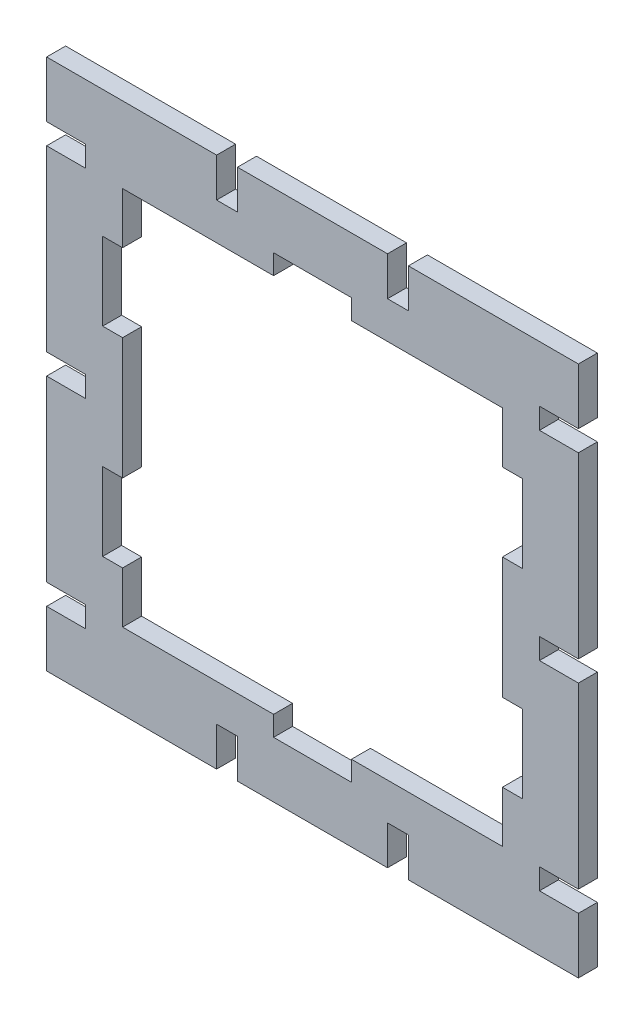
SolidWorks part; units mm, degrees
material "Plain Carbon Steel"
ref_plane "Front Plane" through (0, 0, 0) normal (0, 0, 1) x (1, 0, 0)
ref_plane "Top Plane" through (0, 0, 0) normal (0, 1, 0) x (1, 0, 0)
ref_plane "Right Plane" through (0, 0, 0) normal (1, 0, 0) x (0, 0, -1)
sketch "Model" plane through (0, 0, 0) normal (0, 0, 1) x (1, 0, 0)
  line L0 (953.5457, -159.9412) -> (953.5457, -127.9412)
  line L1 (973.5457, -73.9412) -> (928.7957, -73.9412)
  line L2 (843.7957, -199.1912) -> (843.7957, -193.6912)
  line L3 (883.7957, -73.9412) -> (883.7957, -84.1912)
  line L4 (843.7957, -146.6912) -> (843.7957, -141.1912)
  line L5 (923.2957, -203.6912) -> (928.7957, -203.6912)
  line L6 (958.7957, -180.4412) -> (953.5457, -180.4412)
  line L7 (843.7957, -193.6912) -> (833.5457, -193.6912)
  line L8 (913.7957, -199.1912) -> (893.2957, -199.1912)
  line L9 (878.2957, -84.1912) -> (878.2957, -73.9412)
  line L10 (833.5457, -146.6912) -> (843.7957, -146.6912)
  line L11 (833.5457, -213.9412) -> (833.5457, -199.1912)
  line L12 (878.2957, -203.6912) -> (883.7957, -203.6912)
  line L13 (833.5457, -94.1912) -> (843.7957, -94.1912)
  line L14 (843.7957, -141.1912) -> (833.5457, -141.1912)
  line L15 (878.2957, -213.9412) -> (833.5457, -213.9412)
  line L16 (883.7957, -203.6912) -> (883.7957, -213.9412)
  line L17 (973.5457, -213.9412) -> (973.5457, -199.1912)
  line L18 (973.5457, -199.1912) -> (963.2957, -199.1912)
  line L19 (963.2957, -146.6912) -> (963.2957, -141.1912)
  line L20 (958.7957, -127.9412) -> (958.7957, -107.4412)
  line L21 (953.5457, -127.9412) -> (958.7957, -127.9412)
  line L22 (853.5457, -107.4412) -> (848.2957, -107.4412)
  line L23 (848.2957, -127.9412) -> (853.5457, -127.9412)
  line L24 (848.2957, -180.4412) -> (848.2957, -159.9412)
  line L25 (963.2957, -94.1912) -> (963.2957, -88.6912)
  line L26 (878.2957, -213.9412) -> (878.2957, -203.6912)
  line L27 (848.2957, -107.4412) -> (848.2957, -127.9412)
  line L28 (833.5457, -141.1912) -> (833.5457, -94.1912)
  line L29 (833.5457, -193.6912) -> (833.5457, -146.6912)
  line L30 (833.5457, -199.1912) -> (843.7957, -199.1912)
  line L31 (883.7957, -213.9412) -> (923.2957, -213.9412)
  line L32 (923.2957, -213.9412) -> (923.2957, -203.6912)
  line L33 (928.7957, -203.6912) -> (928.7957, -213.9412)
  line L34 (928.7957, -213.9412) -> (973.5457, -213.9412)
  line L35 (963.2957, -199.1912) -> (963.2957, -193.6912)
  line L36 (963.2957, -193.6912) -> (973.5457, -193.6912)
  line L37 (973.5457, -193.6912) -> (973.5457, -146.6912)
  line L38 (973.5457, -146.6912) -> (963.2957, -146.6912)
  line L39 (963.2957, -141.1912) -> (973.5457, -141.1912)
  line L40 (973.5457, -141.1912) -> (973.5457, -94.1912)
  line L41 (973.5457, -94.1912) -> (963.2957, -94.1912)
  line L42 (963.2957, -88.6912) -> (973.5457, -88.6912)
  line L43 (973.5457, -88.6912) -> (973.5457, -73.9412)
  line L44 (928.7957, -73.9412) -> (928.7957, -84.1912)
  line L45 (928.7957, -84.1912) -> (923.2957, -84.1912)
  line L46 (923.2957, -84.1912) -> (923.2957, -73.9412)
  line L47 (923.2957, -73.9412) -> (883.7957, -73.9412)
  line L48 (883.7957, -84.1912) -> (878.2957, -84.1912)
  line L49 (833.5457, -73.9412) -> (878.2957, -73.9412)
  line L50 (833.5457, -88.6912) -> (833.5457, -73.9412)
  line L51 (843.7957, -88.6912) -> (833.5457, -88.6912)
  line L52 (843.7957, -94.1912) -> (843.7957, -88.6912)
  line L53 (953.5457, -159.9412) -> (958.7957, -159.9412)
  line L54 (958.7957, -159.9412) -> (958.7957, -180.4412)
  line L55 (953.5457, -180.4412) -> (953.5457, -193.9412)
  line L56 (953.5457, -193.9412) -> (913.7957, -193.9412)
  line L57 (913.7957, -193.9412) -> (913.7957, -199.1912)
  line L58 (893.2957, -199.1912) -> (893.2957, -193.9412)
  line L59 (893.2957, -193.9412) -> (853.5457, -193.9412)
  line L60 (853.5457, -193.9412) -> (853.5457, -180.4412)
  line L61 (853.5457, -180.4412) -> (848.2957, -180.4412)
  line L62 (848.2957, -159.9412) -> (853.5457, -159.9412)
  line L63 (853.5457, -127.9412) -> (853.5457, -159.9412)
  line L64 (853.5457, -93.9412) -> (853.5457, -107.4412)
  line L65 (893.2957, -93.9412) -> (853.5457, -93.9412)
  line L66 (893.2957, -88.6912) -> (893.2957, -93.9412)
  line L67 (913.7957, -88.6912) -> (893.2957, -88.6912)
  line L68 (913.7957, -93.9412) -> (913.7957, -88.6912)
  line L69 (953.5457, -93.9412) -> (913.7957, -93.9412)
  line L70 (953.5457, -107.4412) -> (953.5457, -93.9412)
  line L71 (958.7957, -107.4412) -> (953.5457, -107.4412)
  line L72 (899.4248, -80.2491) -> (899.4248, -78.0513)
  line L73 (899.4248, -78.0513) -> (900.4426, -78.0513)
  line L74 (900.4426, -78.0513) -> (900.9998, -78.12)
  line L75 (900.9998, -78.12) -> (901.3354, -78.2261)
  line L76 (901.3354, -78.2261) -> (901.5087, -78.3603)
  line L77 (901.5087, -78.3603) -> (901.5665, -78.5133)
  line L78 (901.5665, -78.5133) -> (901.5665, -79.7683)
  line L79 (901.5665, -79.7683) -> (901.5458, -79.8671)
  line L80 (901.5458, -79.8671) -> (901.4837, -79.9572)
  line L81 (901.4837, -79.9572) -> (901.2355, -80.1117)
  line L82 (901.2355, -80.1117) -> (900.875, -80.2148)
  line L83 (900.875, -80.2148) -> (900.4426, -80.2491)
  line L84 (900.4426, -80.2491) -> (899.4248, -80.2491)
  line L85 (899.4248, -75.9412) -> (899.4248, -80.2491)
  line L86 (899.4248, -80.2491) -> (900.4426, -80.2491)
  line L87 (900.4426, -80.2491) -> (900.875, -80.2148)
  line L88 (900.875, -80.2148) -> (901.2355, -80.1118)
  line L89 (901.2355, -80.1118) -> (901.4837, -79.9572)
  line L90 (901.4837, -79.9572) -> (901.5458, -79.8671)
  line L91 (901.5458, -79.8671) -> (901.5665, -79.7684)
  line L92 (901.5665, -79.7684) -> (901.5665, -78.5135)
  line L93 (901.5665, -78.5135) -> (901.5087, -78.3605)
  line L94 (901.5087, -78.3605) -> (901.3354, -78.2263)
  line L95 (901.3354, -78.2263) -> (900.9998, -78.1201)
  line L96 (900.9998, -78.1201) -> (900.4426, -78.0515)
  line L97 (900.4426, -78.0515) -> (900.9936, -77.9875)
  line L98 (900.9936, -77.9875) -> (901.3354, -77.8829)
  line L99 (901.3354, -77.8829) -> (901.5087, -77.744)
  line L100 (901.5087, -77.744) -> (901.5665, -77.5894)
  line L101 (901.5665, -77.5894) -> (901.5665, -76.422)
  line L102 (901.5665, -76.422) -> (901.5458, -76.3283)
  line L103 (901.5458, -76.3283) -> (901.4837, -76.2409)
  line L104 (901.4837, -76.2409) -> (901.2355, -76.0848)
  line L105 (901.2355, -76.0848) -> (900.8718, -75.9771)
  line L106 (900.8718, -75.9771) -> (900.4426, -75.9412)
  line L107 (900.4426, -75.9412) -> (899.4248, -75.9412)
  line L108 (900.4426, -78.0517) -> (899.4248, -78.0517)
  line L109 (899.4248, -78.0517) -> (899.4248, -75.9412)
  line L110 (899.4248, -75.9412) -> (900.4426, -75.9412)
  line L111 (900.4426, -75.9412) -> (900.8718, -75.9771)
  line L112 (900.8718, -75.9771) -> (901.2355, -76.0848)
  line L113 (901.2355, -76.0848) -> (901.4837, -76.2409)
  line L114 (901.4837, -76.2409) -> (901.5458, -76.3283)
  line L115 (901.5458, -76.3283) -> (901.5665, -76.422)
  line L116 (901.5665, -76.422) -> (901.5665, -77.5896)
  line L117 (901.5665, -77.5896) -> (901.5087, -77.7441)
  line L118 (901.5087, -77.7441) -> (901.3354, -77.8831)
  line L119 (901.3354, -77.8831) -> (900.9936, -77.9877)
  line L120 (900.9936, -77.9877) -> (900.4426, -78.0517)
  line L121 (902.4218, -80.2491) -> (902.4218, -75.9412)
  line L122 (902.4218, -75.9412) -> (904.5509, -75.9412)
  line L123 (904.5509, -75.9412) -> (902.4218, -75.9412)
  line L124 (902.4218, -75.9412) -> (902.4218, -78.0327)
  line L125 (902.4218, -78.0327) -> (904.2512, -78.0327)
  line L126 (904.2512, -78.0327) -> (902.4218, -78.0327)
  line L127 (902.4218, -78.0327) -> (902.4218, -80.2491)
  line L128 (902.4218, -80.2491) -> (904.5509, -80.2491)
  line L129 (904.5509, -80.2491) -> (902.4218, -80.2491)
  line L130 (906.5426, -80.2491) -> (906.1016, -80.214)
  line L131 (906.1016, -80.214) -> (905.7403, -80.1086)
  line L132 (905.7403, -80.1086) -> (905.4991, -79.9533)
  line L133 (905.4991, -79.9533) -> (905.4388, -79.8646)
  line L134 (905.4388, -79.8646) -> (905.4187, -79.7684)
  line L135 (905.4187, -79.7684) -> (905.4388, -79.8646)
  line L136 (905.4388, -79.8646) -> (905.4991, -79.9533)
  line L137 (905.4991, -79.9533) -> (905.7403, -80.1086)
  line L138 (905.7403, -80.1086) -> (906.1016, -80.214)
  line L139 (906.9836, -80.214) -> (907.345, -80.1086)
  line L140 (907.345, -80.1086) -> (907.5861, -79.9533)
  line L141 (907.5861, -79.9533) -> (907.6464, -79.8646)
  line L142 (907.6464, -79.8646) -> (907.6665, -79.7684)
  line L143 (907.6665, -79.7684) -> (907.6665, -78.0577)
  line L144 (907.6665, -78.0577) -> (907.6464, -77.9615)
  line L145 (907.6464, -77.9615) -> (907.5861, -77.8727)
  line L146 (907.5861, -77.8727) -> (907.345, -77.7174)
  line L147 (907.345, -77.7174) -> (906.9836, -77.612)
  line L148 (906.9836, -77.612) -> (906.5426, -77.5769)
  line L149 (906.5426, -77.5769) -> (905.8683, -77.6768)
  line L150 (905.8683, -77.6768) -> (905.6372, -77.8033)
  line L151 (905.6372, -77.8033) -> (905.4187, -78.0577)
  line L152 (905.4187, -78.0577) -> (905.4187, -75.9412)
  line L153 (905.4187, -75.9412) -> (907.5916, -75.9412)
  line L154 (907.5916, -75.9412) -> (905.4187, -75.9412)
  line L155 (905.4187, -75.9412) -> (905.4187, -78.0577)
  line L156 (905.4187, -78.0577) -> (905.6372, -77.8033)
  line L157 (905.6372, -77.8033) -> (905.8683, -77.6768)
  line L158 (905.8683, -77.6768) -> (906.5426, -77.5769)
  line L159 (906.5426, -77.5769) -> (906.9836, -77.612)
  line L160 (906.9836, -77.612) -> (907.345, -77.7174)
  line L161 (907.345, -77.7174) -> (907.5861, -77.8727)
  line L162 (907.5861, -77.8727) -> (907.6464, -77.9615)
  line L163 (907.6464, -77.9615) -> (907.6665, -78.0577)
  line L164 (907.6665, -78.0577) -> (907.6665, -79.7684)
  line L165 (907.6665, -79.7684) -> (907.6464, -79.8646)
  line L166 (907.6464, -79.8646) -> (907.5861, -79.9533)
  line L167 (907.5861, -79.9533) -> (907.345, -80.1086)
  line L168 (907.345, -80.1086) -> (906.9836, -80.214)
  line L169 (906.9836, -80.214) -> (906.5426, -80.2491)
  line L170 (896.9248, -78.0616) -> (891.9248, -78.0616)
  line L171 (893.9248, -77.0616) -> (891.9248, -78.0616)
  line L172 (893.9248, -79.0616) -> (891.9248, -78.0616)
  line L173 (910.1665, -78.0616) -> (915.1665, -78.0616)
  line L174 (913.1665, -79.0616) -> (915.1665, -78.0616)
  line L175 (913.1665, -77.0616) -> (915.1665, -78.0616)
  line L176 (956.2957, -196.4228) -> (961.2957, -196.4228)
  line L177 (959.2957, -197.4228) -> (961.2957, -196.4228)
  line L178 (959.2957, -195.4228) -> (961.2957, -196.4228)
  line L179 (956.2957, -199.9228) -> (958.4935, -199.9228)
  line L180 (958.4935, -199.9228) -> (958.4935, -200.9406)
  line L181 (958.4935, -200.9406) -> (958.4248, -201.4978)
  line L182 (958.4248, -201.4978) -> (958.3187, -201.8335)
  line L183 (958.3187, -201.8335) -> (958.1844, -202.0067)
  line L184 (958.1844, -202.0067) -> (958.0315, -202.0645)
  line L185 (958.0315, -202.0645) -> (956.7765, -202.0645)
  line L186 (956.7765, -202.0645) -> (956.6777, -202.0438)
  line L187 (956.6777, -202.0438) -> (956.5876, -201.9818)
  line L188 (956.5876, -201.9818) -> (956.433, -201.7336)
  line L189 (956.433, -201.7336) -> (956.33, -201.373)
  line L190 (956.33, -201.373) -> (956.2957, -200.9406)
  line L191 (956.2957, -200.9406) -> (956.2957, -199.9228)
  line L192 (960.6036, -199.9228) -> (956.2957, -199.9228)
  line L193 (956.2957, -199.9228) -> (956.2957, -200.9406)
  line L194 (956.2957, -200.9406) -> (956.33, -201.373)
  line L195 (956.33, -201.373) -> (956.433, -201.7336)
  line L196 (956.433, -201.7336) -> (956.5875, -201.9818)
  line L197 (956.5875, -201.9818) -> (956.6777, -202.0438)
  line L198 (956.6777, -202.0438) -> (956.7764, -202.0645)
  line L199 (956.7764, -202.0645) -> (958.0313, -202.0645)
  line L200 (958.0313, -202.0645) -> (958.1843, -202.0067)
  line L201 (958.1843, -202.0067) -> (958.3185, -201.8335)
  line L202 (958.3185, -201.8335) -> (958.4246, -201.4978)
  line L203 (958.4246, -201.4978) -> (958.4933, -200.9406)
  line L204 (958.4933, -200.9406) -> (958.5573, -201.4916)
  line L205 (958.5573, -201.4916) -> (958.6619, -201.8335)
  line L206 (958.6619, -201.8335) -> (958.8008, -202.0067)
  line L207 (958.8008, -202.0067) -> (958.9553, -202.0645)
  line L208 (958.9553, -202.0645) -> (960.1228, -202.0645)
  line L209 (960.1228, -202.0645) -> (960.2165, -202.0438)
  line L210 (960.2165, -202.0438) -> (960.3039, -201.9818)
  line L211 (960.3039, -201.9818) -> (960.46, -201.7336)
  line L212 (960.46, -201.7336) -> (960.5677, -201.3699)
  line L213 (960.5677, -201.3699) -> (960.6036, -200.9406)
  line L214 (960.6036, -200.9406) -> (960.6036, -199.9228)
  line L215 (958.4931, -200.9406) -> (958.4931, -199.9228)
  line L216 (958.4931, -199.9228) -> (960.6036, -199.9228)
  line L217 (960.6036, -199.9228) -> (960.6036, -200.9406)
  line L218 (960.6036, -200.9406) -> (960.5677, -201.3699)
  line L219 (960.5677, -201.3699) -> (960.46, -201.7336)
  line L220 (960.46, -201.7336) -> (960.3039, -201.9818)
  line L221 (960.3039, -201.9818) -> (960.2164, -202.0438)
  line L222 (960.2164, -202.0438) -> (960.1228, -202.0645)
  line L223 (960.1228, -202.0645) -> (958.9552, -202.0645)
  line L224 (958.9552, -202.0645) -> (958.8006, -202.0067)
  line L225 (958.8006, -202.0067) -> (958.6617, -201.8335)
  line L226 (958.6617, -201.8335) -> (958.5571, -201.4916)
  line L227 (958.5571, -201.4916) -> (958.4931, -200.9406)
  line L228 (956.2957, -202.9198) -> (960.6036, -202.9198)
  line L229 (960.6036, -202.9198) -> (960.6036, -203.9376)
  line L230 (960.6036, -203.9376) -> (960.5677, -204.3715)
  line L231 (960.5677, -204.3715) -> (960.46, -204.7368)
  line L232 (960.46, -204.7368) -> (960.3039, -204.9803)
  line L233 (960.3039, -204.9803) -> (960.2165, -205.0412)
  line L234 (960.2165, -205.0412) -> (960.1228, -205.0615)
  line L235 (960.1228, -205.0615) -> (956.7764, -205.0615)
  line L236 (956.7764, -205.0615) -> (956.68, -205.0412)
  line L237 (956.68, -205.0412) -> (956.5907, -204.9803)
  line L238 (956.5907, -204.9803) -> (956.433, -204.7368)
  line L239 (956.433, -204.7368) -> (956.33, -204.3808)
  line L240 (956.33, -204.3808) -> (956.2957, -203.9376)
  line L241 (956.2957, -203.9376) -> (956.2957, -202.9198)
  line L242 (960.6036, -202.9198) -> (956.2957, -202.9198)
  line L243 (956.2957, -202.9198) -> (956.2957, -203.9376)
  line L244 (956.2957, -203.9376) -> (956.33, -204.3808)
  line L245 (956.33, -204.3808) -> (956.433, -204.7368)
  line L246 (956.433, -204.7368) -> (956.5907, -204.9803)
  line L247 (956.5907, -204.9803) -> (956.68, -205.0412)
  line L248 (956.68, -205.0412) -> (956.7764, -205.0615)
  line L249 (956.7764, -205.0615) -> (960.1228, -205.0615)
  line L250 (960.1228, -205.0615) -> (960.2165, -205.0412)
  line L251 (960.2165, -205.0412) -> (960.3039, -204.9803)
  line L252 (960.3039, -204.9803) -> (960.46, -204.7368)
  line L253 (960.46, -204.7368) -> (960.5677, -204.3715)
  line L254 (960.5677, -204.3715) -> (960.6036, -203.9376)
  line L255 (960.6036, -203.9376) -> (960.6036, -202.9198)
  line L256 (956.3308, -206.5996) -> (956.4361, -206.2383)
  line L257 (956.4361, -206.2383) -> (956.5915, -205.9971)
  line L258 (956.5915, -205.9971) -> (956.6802, -205.9368)
  line L259 (956.6802, -205.9368) -> (956.7764, -205.9167)
  line L260 (956.7764, -205.9167) -> (956.6802, -205.9368)
  line L261 (956.6802, -205.9368) -> (956.5915, -205.9971)
  line L262 (956.5915, -205.9971) -> (956.4361, -206.2383)
  line L263 (956.4361, -206.2383) -> (956.3308, -206.5996)
  line L264 (956.3308, -207.4816) -> (956.4361, -207.843)
  line L265 (956.4361, -207.843) -> (956.5915, -208.0842)
  line L266 (956.5915, -208.0842) -> (956.6802, -208.1444)
  line L267 (956.6802, -208.1444) -> (956.7764, -208.1645)
  line L268 (956.7764, -208.1645) -> (958.4871, -208.1645)
  line L269 (958.4871, -208.1645) -> (958.5833, -208.1444)
  line L270 (958.5833, -208.1444) -> (958.6721, -208.0842)
  line L271 (958.6721, -208.0842) -> (958.8274, -207.843)
  line L272 (958.8274, -207.843) -> (958.9327, -207.4816)
  line L273 (958.9327, -207.4816) -> (958.9679, -207.0406)
  line L274 (958.9679, -207.0406) -> (958.8679, -206.3663)
  line L275 (958.8679, -206.3663) -> (958.7415, -206.1353)
  line L276 (958.7415, -206.1353) -> (958.4871, -205.9167)
  line L277 (958.4871, -205.9167) -> (960.6036, -205.9167)
  line L278 (960.6036, -205.9167) -> (960.6036, -208.0896)
  line L279 (960.6036, -208.0896) -> (960.6036, -205.9167)
  line L280 (960.6036, -205.9167) -> (958.4871, -205.9167)
  line L281 (958.4871, -205.9167) -> (958.7415, -206.1353)
  line L282 (958.7415, -206.1353) -> (958.8679, -206.3663)
  line L283 (958.8679, -206.3663) -> (958.9679, -207.0406)
  line L284 (958.9679, -207.0406) -> (958.9327, -207.4816)
  line L285 (958.9327, -207.4816) -> (958.8274, -207.843)
  line L286 (958.8274, -207.843) -> (958.6721, -208.0842)
  line L287 (958.6721, -208.0842) -> (958.5833, -208.1444)
  line L288 (958.5833, -208.1444) -> (958.4871, -208.1645)
  line L289 (958.4871, -208.1645) -> (956.7764, -208.1645)
  line L290 (956.7764, -208.1645) -> (956.6802, -208.1444)
  line L291 (956.6802, -208.1444) -> (956.5915, -208.0842)
  line L292 (956.5915, -208.0842) -> (956.4361, -207.843)
  line L293 (956.4361, -207.843) -> (956.3308, -207.4816)
  line L294 (956.3308, -207.4816) -> (956.2957, -207.0406)
  line L295 (956.2957, -207.0406) -> (956.3308, -206.5996)
  line L296 (956.2957, -132.2056) -> (958.4935, -132.2056)
  line L297 (958.4935, -132.2056) -> (958.4935, -133.2233)
  line L298 (958.4935, -133.2233) -> (958.4248, -133.7806)
  line L299 (958.4248, -133.7806) -> (958.3187, -134.1162)
  line L300 (958.3187, -134.1162) -> (958.1844, -134.2895)
  line L301 (958.1844, -134.2895) -> (958.0315, -134.3472)
  line L302 (958.0315, -134.3472) -> (956.7765, -134.3472)
  line L303 (956.7765, -134.3472) -> (956.6777, -134.3265)
  line L304 (956.6777, -134.3265) -> (956.5876, -134.2645)
  line L305 (956.5876, -134.2645) -> (956.433, -134.0163)
  line L306 (956.433, -134.0163) -> (956.33, -133.6557)
  line L307 (956.33, -133.6557) -> (956.2957, -133.2233)
  line L308 (956.2957, -133.2233) -> (956.2957, -132.2056)
  line L309 (960.6036, -132.2056) -> (956.2957, -132.2056)
  line L310 (956.2957, -132.2056) -> (956.2957, -133.2233)
  line L311 (956.2957, -133.2233) -> (956.33, -133.6557)
  line L312 (956.33, -133.6557) -> (956.433, -134.0163)
  line L313 (956.433, -134.0163) -> (956.5875, -134.2645)
  line L314 (956.5875, -134.2645) -> (956.6777, -134.3265)
  line L315 (956.6777, -134.3265) -> (956.7764, -134.3472)
  line L316 (956.7764, -134.3472) -> (958.0313, -134.3472)
  line L317 (958.0313, -134.3472) -> (958.1843, -134.2895)
  line L318 (958.1843, -134.2895) -> (958.3185, -134.1162)
  line L319 (958.3185, -134.1162) -> (958.4246, -133.7806)
  line L320 (958.4246, -133.7806) -> (958.4933, -133.2233)
  line L321 (958.4933, -133.2233) -> (958.5573, -133.7743)
  line L322 (958.5573, -133.7743) -> (958.6619, -134.1162)
  line L323 (958.6619, -134.1162) -> (958.8008, -134.2895)
  line L324 (958.8008, -134.2895) -> (958.9553, -134.3472)
  line L325 (958.9553, -134.3472) -> (960.1228, -134.3472)
  line L326 (960.1228, -134.3472) -> (960.2165, -134.3265)
  line L327 (960.2165, -134.3265) -> (960.3039, -134.2645)
  line L328 (960.3039, -134.2645) -> (960.46, -134.0163)
  line L329 (960.46, -134.0163) -> (960.5677, -133.6526)
  line L330 (960.5677, -133.6526) -> (960.6036, -133.2233)
  line L331 (960.6036, -133.2233) -> (960.6036, -132.2056)
  line L332 (958.4931, -133.2233) -> (958.4931, -132.2056)
  line L333 (958.4931, -132.2056) -> (960.6036, -132.2056)
  line L334 (960.6036, -132.2056) -> (960.6036, -133.2233)
  line L335 (960.6036, -133.2233) -> (960.5677, -133.6526)
  line L336 (960.5677, -133.6526) -> (960.46, -134.0163)
  line L337 (960.46, -134.0163) -> (960.3039, -134.2645)
  line L338 (960.3039, -134.2645) -> (960.2164, -134.3265)
  line L339 (960.2164, -134.3265) -> (960.1228, -134.3472)
  line L340 (960.1228, -134.3472) -> (958.9552, -134.3472)
  line L341 (958.9552, -134.3472) -> (958.8006, -134.2895)
  line L342 (958.8006, -134.2895) -> (958.6617, -134.1162)
  line L343 (958.6617, -134.1162) -> (958.5571, -133.7743)
  line L344 (958.5571, -133.7743) -> (958.4931, -133.2233)
  line L345 (957.0823, -137.4503) -> (956.7764, -137.4503)
  line L346 (956.7764, -137.4503) -> (956.68, -137.43)
  line L347 (956.68, -137.43) -> (956.5907, -137.3691)
  line L348 (956.5907, -137.3691) -> (956.433, -137.1256)
  line L349 (956.433, -137.1256) -> (956.33, -136.7697)
  line L350 (956.33, -136.7697) -> (956.2957, -136.3264)
  line L351 (956.2957, -136.3264) -> (956.33, -135.8815)
  line L352 (956.33, -135.8815) -> (956.433, -135.521)
  line L353 (956.433, -135.521) -> (956.5875, -135.2821)
  line L354 (956.5875, -135.2821) -> (956.6777, -135.2224)
  line L355 (956.6777, -135.2224) -> (956.7764, -135.2025)
  line L356 (956.7764, -135.2025) -> (960.1228, -135.2025)
  line L357 (960.1228, -135.2025) -> (960.2188, -135.2224)
  line L358 (960.2188, -135.2224) -> (960.307, -135.2821)
  line L359 (960.307, -135.2821) -> (960.46, -135.521)
  line L360 (960.46, -135.521) -> (960.5677, -135.8878)
  line L361 (960.5677, -135.8878) -> (960.6036, -136.3264)
  line L362 (960.6036, -136.3264) -> (960.5677, -136.7603)
  line L363 (960.5677, -136.7603) -> (960.46, -137.1256)
  line L364 (960.46, -137.1256) -> (960.3039, -137.3691)
  line L365 (960.3039, -137.3691) -> (960.2165, -137.43)
  line L366 (960.2165, -137.43) -> (960.1228, -137.4503)
  line L367 (960.1228, -137.4503) -> (959.8169, -137.4503)
  line L368 (959.8169, -137.4503) -> (960.1228, -137.4503)
  line L369 (960.1228, -137.4503) -> (960.2165, -137.43)
  line L370 (960.2165, -137.43) -> (960.3039, -137.3691)
  line L371 (960.3039, -137.3691) -> (960.46, -137.1256)
  line L372 (960.46, -137.1256) -> (960.5677, -136.7603)
  line L373 (960.5677, -136.7603) -> (960.6036, -136.3264)
  line L374 (960.6036, -136.3264) -> (960.5677, -135.8878)
  line L375 (960.5677, -135.8878) -> (960.46, -135.521)
  line L376 (960.46, -135.521) -> (960.307, -135.2821)
  line L377 (960.307, -135.2821) -> (960.2188, -135.2224)
  line L378 (960.2188, -135.2224) -> (960.1228, -135.2025)
  line L379 (960.1228, -135.2025) -> (956.7764, -135.2025)
  line L380 (956.7764, -135.2025) -> (956.6777, -135.2224)
  line L381 (956.6777, -135.2224) -> (956.5875, -135.2821)
  line L382 (956.5875, -135.2821) -> (956.433, -135.521)
  line L383 (956.433, -135.521) -> (956.33, -135.8815)
  line L384 (956.33, -135.8815) -> (956.2957, -136.3264)
  line L385 (956.2957, -136.3264) -> (956.33, -136.7697)
  line L386 (956.33, -136.7697) -> (956.433, -137.1256)
  line L387 (956.433, -137.1256) -> (956.5907, -137.3691)
  line L388 (956.5907, -137.3691) -> (956.68, -137.43)
  line L389 (956.68, -137.43) -> (956.7764, -137.4503)
  line L390 (956.7764, -137.4503) -> (957.0823, -137.4503)
  line L391 (956.2957, -139.3173) -> (956.3308, -138.8763)
  line L392 (956.3308, -138.8763) -> (956.4361, -138.5149)
  line L393 (956.4361, -138.5149) -> (956.5915, -138.2737)
  line L394 (956.5915, -138.2737) -> (956.6802, -138.2135)
  line L395 (956.6802, -138.2135) -> (956.7764, -138.1934)
  line L396 (956.7764, -138.1934) -> (956.6802, -138.2135)
  line L397 (956.6802, -138.2135) -> (956.5915, -138.2737)
  line L398 (956.5915, -138.2737) -> (956.4361, -138.5149)
  line L399 (956.4361, -138.5149) -> (956.3308, -138.8763)
  line L400 (956.3308, -139.7583) -> (956.4361, -140.1196)
  line L401 (956.4361, -140.1196) -> (956.5915, -140.3608)
  line L402 (956.5915, -140.3608) -> (956.6802, -140.4211)
  line L403 (956.6802, -140.4211) -> (956.7764, -140.4412)
  line L404 (956.7764, -140.4412) -> (958.4871, -140.4412)
  line L405 (958.4871, -140.4412) -> (958.5833, -140.4211)
  line L406 (958.5833, -140.4211) -> (958.6721, -140.3608)
  line L407 (958.6721, -140.3608) -> (958.8274, -140.1196)
  line L408 (958.8274, -140.1196) -> (958.9327, -139.7583)
  line L409 (958.9327, -139.7583) -> (958.9679, -139.3173)
  line L410 (958.9679, -139.3173) -> (958.8679, -138.6429)
  line L411 (958.8679, -138.6429) -> (958.7415, -138.4119)
  line L412 (958.7415, -138.4119) -> (958.4871, -138.1934)
  line L413 (958.4871, -138.1934) -> (960.6036, -138.1934)
  line L414 (960.6036, -138.1934) -> (960.6036, -140.3662)
  line L415 (960.6036, -140.3662) -> (960.6036, -138.1934)
  line L416 (960.6036, -138.1934) -> (958.4871, -138.1934)
  line L417 (958.4871, -138.1934) -> (958.7415, -138.4119)
  line L418 (958.7415, -138.4119) -> (958.8679, -138.6429)
  line L419 (958.8679, -138.6429) -> (958.9679, -139.3173)
  line L420 (958.9679, -139.3173) -> (958.9327, -139.7583)
  line L421 (958.9327, -139.7583) -> (958.8274, -140.1196)
  line L422 (958.8274, -140.1196) -> (958.6721, -140.3608)
  line L423 (958.6721, -140.3608) -> (958.5833, -140.4211)
  line L424 (958.5833, -140.4211) -> (958.4871, -140.4412)
  line L425 (958.4871, -140.4412) -> (956.7764, -140.4412)
  line L426 (956.7764, -140.4412) -> (956.6802, -140.4211)
  line L427 (956.6802, -140.4211) -> (956.5915, -140.3608)
  line L428 (956.5915, -140.3608) -> (956.4361, -140.1196)
  line L429 (956.4361, -140.1196) -> (956.3308, -139.7583)
  line L430 (956.3308, -139.7583) -> (956.2957, -139.3173)
  line L431 (956.2957, -143.9412) -> (961.2957, -143.9412)
  line L432 (959.2957, -144.9412) -> (961.2957, -143.9412)
  line L433 (959.2957, -142.9412) -> (961.2957, -143.9412)
  line L434 (840.2957, -174.5497) -> (838.0978, -174.5497)
  line L435 (838.1665, -172.9747) -> (838.2727, -172.6391)
  line L436 (838.2727, -172.6391) -> (838.4069, -172.4658)
  line L437 (838.4069, -172.4658) -> (838.5599, -172.4081)
  line L438 (838.5599, -172.4081) -> (839.8149, -172.4081)
  line L439 (839.8149, -172.4081) -> (839.9136, -172.4287)
  line L440 (839.9136, -172.4287) -> (840.0038, -172.4908)
  line L441 (840.0038, -172.4908) -> (840.1583, -172.739)
  line L442 (840.1583, -172.739) -> (840.2613, -173.0996)
  line L443 (840.2613, -173.0996) -> (840.2957, -173.532)
  line L444 (840.2957, -173.532) -> (840.2957, -174.5497)
  line L445 (835.9877, -174.5497) -> (840.2957, -174.5497)
  line L446 (840.2957, -174.5497) -> (840.2957, -173.532)
  line L447 (840.2957, -173.532) -> (840.2613, -173.0996)
  line L448 (840.2613, -173.0996) -> (840.1583, -172.739)
  line L449 (840.1583, -172.739) -> (840.0038, -172.4908)
  line L450 (840.0038, -172.4908) -> (839.9136, -172.4287)
  line L451 (839.9136, -172.4287) -> (839.8149, -172.4081)
  line L452 (839.8149, -172.4081) -> (838.56, -172.4081)
  line L453 (838.56, -172.4081) -> (838.4071, -172.4658)
  line L454 (838.4071, -172.4658) -> (838.2728, -172.6391)
  line L455 (838.2728, -172.6391) -> (838.1665, -172.9747)
  line L456 (838.1665, -172.9747) -> (838.0978, -173.532)
  line L457 (838.034, -172.981) -> (837.9294, -172.6391)
  line L458 (837.9294, -172.6391) -> (837.7905, -172.4658)
  line L459 (837.7905, -172.4658) -> (837.636, -172.4081)
  line L460 (837.636, -172.4081) -> (836.4685, -172.4081)
  line L461 (836.4685, -172.4081) -> (836.3748, -172.4287)
  line L462 (836.3748, -172.4287) -> (836.2874, -172.4908)
  line L463 (836.2874, -172.4908) -> (836.1313, -172.739)
  line L464 (836.1313, -172.739) -> (836.0236, -173.1027)
  line L465 (836.0236, -173.1027) -> (835.9877, -173.532)
  line L466 (835.9877, -173.532) -> (835.9877, -174.5497)
  line L467 (838.0978, -173.532) -> (838.0978, -174.5497)
  line L468 (838.0978, -174.5497) -> (835.9877, -174.5497)
  line L469 (835.9877, -174.5497) -> (835.9877, -173.532)
  line L470 (835.9877, -173.532) -> (836.0236, -173.1027)
  line L471 (836.0236, -173.1027) -> (836.1314, -172.739)
  line L472 (836.1314, -172.739) -> (836.2875, -172.4908)
  line L473 (836.2875, -172.4908) -> (836.3749, -172.4287)
  line L474 (836.3749, -172.4287) -> (836.4685, -172.4081)
  line L475 (836.4685, -172.4081) -> (837.6361, -172.4081)
  line L476 (837.6361, -172.4081) -> (837.7907, -172.4658)
  line L477 (837.7907, -172.4658) -> (837.9296, -172.6391)
  line L478 (837.9296, -172.6391) -> (838.034, -172.981)
  line L479 (838.034, -172.981) -> (838.0978, -173.532)
  line L480 (835.9816, -170.4913) -> (838.0982, -169.9396)
  line L481 (835.9816, -170.4913) -> (838.0981, -171.0121)
  line L482 (838.4787, -169.8419) -> (840.2957, -169.3674)
  line L483 (840.2605, -167.8729) -> (840.1552, -168.2343)
  line L484 (840.1552, -168.2343) -> (839.9999, -168.4754)
  line L485 (839.9999, -168.4754) -> (839.9111, -168.5357)
  line L486 (839.9111, -168.5357) -> (839.8149, -168.5558)
  line L487 (839.8149, -168.5558) -> (839.9111, -168.5357)
  line L488 (839.9111, -168.5357) -> (839.9999, -168.4754)
  line L489 (839.9999, -168.4754) -> (840.1552, -168.2343)
  line L490 (840.1552, -168.2343) -> (840.2605, -167.8729)
  line L491 (840.2605, -166.9909) -> (840.1552, -166.6296)
  line L492 (840.1552, -166.6296) -> (839.9999, -166.3884)
  line L493 (839.9999, -166.3884) -> (839.9111, -166.3281)
  line L494 (839.9111, -166.3281) -> (839.8149, -166.308)
  line L495 (839.8149, -166.308) -> (838.1043, -166.308)
  line L496 (838.1043, -166.308) -> (838.008, -166.3281)
  line L497 (838.008, -166.3281) -> (837.9193, -166.3884)
  line L498 (837.9193, -166.3884) -> (837.7639, -166.6296)
  line L499 (837.7639, -166.6296) -> (837.6586, -166.9909)
  line L500 (837.6586, -166.9909) -> (837.6235, -167.4319)
  line L501 (837.6235, -167.4319) -> (837.7234, -168.1063)
  line L502 (837.7234, -168.1063) -> (837.8498, -168.3373)
  line L503 (837.8498, -168.3373) -> (838.1043, -168.5558)
  line L504 (838.1043, -168.5558) -> (835.9877, -168.5558)
  line L505 (835.9877, -168.5558) -> (835.9877, -166.383)
  line L506 (835.9877, -166.383) -> (835.9877, -168.5558)
  line L507 (835.9877, -168.5558) -> (838.1043, -168.5558)
  line L508 (838.1043, -168.5558) -> (837.8498, -168.3373)
  line L509 (837.8498, -168.3373) -> (837.7234, -168.1063)
  line L510 (837.7234, -168.1063) -> (837.6235, -167.4319)
  line L511 (837.6235, -167.4319) -> (837.6586, -166.9909)
  line L512 (837.6586, -166.9909) -> (837.7639, -166.6296)
  line L513 (837.7639, -166.6296) -> (837.9193, -166.3884)
  line L514 (837.9193, -166.3884) -> (838.008, -166.3281)
  line L515 (838.008, -166.3281) -> (838.1043, -166.308)
  line L516 (838.1043, -166.308) -> (839.8149, -166.308)
  line L517 (839.8149, -166.308) -> (839.9111, -166.3281)
  line L518 (839.9111, -166.3281) -> (839.9999, -166.3884)
  line L519 (839.9999, -166.3884) -> (840.1552, -166.6296)
  line L520 (840.1552, -166.6296) -> (840.2605, -166.9909)
  line L521 (840.2605, -166.9909) -> (840.2957, -167.4319)
  line L522 (840.2957, -167.4319) -> (840.2605, -167.8729)
  line L523 (838.0982, -169.9396) -> (838.473, -169.8419)
  line L524 (838.0981, -171.0121) -> (840.2957, -171.5528)
  line L525 (838.0981, -171.0121) -> (838.0982, -169.9396)
  line L526 (841.2957, -170.4289) -> (846.2957, -170.4289)
  line L527 (844.2957, -171.4289) -> (846.2957, -170.4289)
  line L528 (844.2957, -169.4289) -> (846.2957, -170.4289)
  line L529 (840.2957, -122.0497) -> (838.0978, -122.0497)
  line L530 (838.1665, -120.4747) -> (838.2727, -120.1391)
  line L531 (838.2727, -120.1391) -> (838.4069, -119.9658)
  line L532 (838.4069, -119.9658) -> (838.5599, -119.9081)
  line L533 (838.5599, -119.9081) -> (839.8149, -119.9081)
  line L534 (839.8149, -119.9081) -> (839.9136, -119.9287)
  line L535 (839.9136, -119.9287) -> (840.0038, -119.9908)
  line L536 (840.0038, -119.9908) -> (840.1583, -120.239)
  line L537 (840.1583, -120.239) -> (840.2613, -120.5996)
  line L538 (840.2613, -120.5996) -> (840.2957, -121.032)
  line L539 (840.2957, -121.032) -> (840.2957, -122.0497)
  line L540 (835.9877, -122.0497) -> (840.2957, -122.0497)
  line L541 (840.2957, -122.0497) -> (840.2957, -121.032)
  line L542 (840.2957, -121.032) -> (840.2613, -120.5996)
  line L543 (840.2613, -120.5996) -> (840.1583, -120.239)
  line L544 (840.1583, -120.239) -> (840.0038, -119.9908)
  line L545 (840.0038, -119.9908) -> (839.9136, -119.9287)
  line L546 (839.9136, -119.9287) -> (839.8149, -119.9081)
  line L547 (839.8149, -119.9081) -> (838.56, -119.9081)
  line L548 (838.56, -119.9081) -> (838.4071, -119.9658)
  line L549 (838.4071, -119.9658) -> (838.2728, -120.1391)
  line L550 (838.2728, -120.1391) -> (838.1665, -120.4747)
  line L551 (838.1665, -120.4747) -> (838.0978, -121.032)
  line L552 (838.034, -120.481) -> (837.9294, -120.1391)
  line L553 (837.9294, -120.1391) -> (837.7905, -119.9658)
  line L554 (837.7905, -119.9658) -> (837.636, -119.9081)
  line L555 (837.636, -119.9081) -> (836.4685, -119.9081)
  line L556 (836.4685, -119.9081) -> (836.3748, -119.9287)
  line L557 (836.3748, -119.9287) -> (836.2874, -119.9908)
  line L558 (836.2874, -119.9908) -> (836.1313, -120.239)
  line L559 (836.1313, -120.239) -> (836.0236, -120.6027)
  line L560 (836.0236, -120.6027) -> (835.9877, -121.032)
  line L561 (835.9877, -121.032) -> (835.9877, -122.0497)
  line L562 (838.0978, -121.032) -> (838.0978, -122.0497)
  line L563 (838.0978, -122.0497) -> (835.9877, -122.0497)
  line L564 (835.9877, -122.0497) -> (835.9877, -121.032)
  line L565 (835.9877, -121.032) -> (836.0236, -120.6027)
  line L566 (836.0236, -120.6027) -> (836.1314, -120.239)
  line L567 (836.1314, -120.239) -> (836.2875, -119.9908)
  line L568 (836.2875, -119.9908) -> (836.3749, -119.9287)
  line L569 (836.3749, -119.9287) -> (836.4685, -119.9081)
  line L570 (836.4685, -119.9081) -> (837.6361, -119.9081)
  line L571 (837.6361, -119.9081) -> (837.7907, -119.9658)
  line L572 (837.7907, -119.9658) -> (837.9296, -120.1391)
  line L573 (837.9296, -120.1391) -> (838.034, -120.481)
  line L574 (838.034, -120.481) -> (838.0978, -121.032)
  line L575 (835.9816, -117.9913) -> (838.0982, -117.4396)
  line L576 (835.9816, -117.9913) -> (838.0981, -118.5121)
  line L577 (838.4787, -117.3419) -> (840.2957, -116.8674)
  line L578 (840.2605, -115.3729) -> (840.1552, -115.7343)
  line L579 (840.1552, -115.7343) -> (839.9999, -115.9754)
  line L580 (839.9999, -115.9754) -> (839.9111, -116.0357)
  line L581 (839.9111, -116.0357) -> (839.8149, -116.0558)
  line L582 (839.8149, -116.0558) -> (839.9111, -116.0357)
  line L583 (839.9111, -116.0357) -> (839.9999, -115.9754)
  line L584 (839.9999, -115.9754) -> (840.1552, -115.7343)
  line L585 (840.1552, -115.7343) -> (840.2605, -115.3729)
  line L586 (840.2605, -114.4909) -> (840.1552, -114.1296)
  line L587 (840.1552, -114.1296) -> (839.9999, -113.8884)
  line L588 (839.9999, -113.8884) -> (839.9111, -113.8281)
  line L589 (839.9111, -113.8281) -> (839.8149, -113.808)
  line L590 (839.8149, -113.808) -> (838.1043, -113.808)
  line L591 (838.1043, -113.808) -> (838.008, -113.8281)
  line L592 (838.008, -113.8281) -> (837.9193, -113.8884)
  line L593 (837.9193, -113.8884) -> (837.7639, -114.1296)
  line L594 (837.7639, -114.1296) -> (837.6586, -114.4909)
  line L595 (837.6586, -114.4909) -> (837.6235, -114.9319)
  line L596 (837.6235, -114.9319) -> (837.7234, -115.6063)
  line L597 (837.7234, -115.6063) -> (837.8498, -115.8373)
  line L598 (837.8498, -115.8373) -> (838.1043, -116.0558)
  line L599 (838.1043, -116.0558) -> (835.9877, -116.0558)
  line L600 (835.9877, -116.0558) -> (835.9877, -113.883)
  line L601 (835.9877, -113.883) -> (835.9877, -116.0558)
  line L602 (835.9877, -116.0558) -> (838.1043, -116.0558)
  line L603 (838.1043, -116.0558) -> (837.8498, -115.8373)
  line L604 (837.8498, -115.8373) -> (837.7234, -115.6063)
  line L605 (837.7234, -115.6063) -> (837.6235, -114.9319)
  line L606 (837.6235, -114.9319) -> (837.6586, -114.4909)
  line L607 (837.6586, -114.4909) -> (837.7639, -114.1296)
  line L608 (837.7639, -114.1296) -> (837.9193, -113.8884)
  line L609 (837.9193, -113.8884) -> (838.008, -113.8281)
  line L610 (838.008, -113.8281) -> (838.1043, -113.808)
  line L611 (838.1043, -113.808) -> (839.8149, -113.808)
  line L612 (839.8149, -113.808) -> (839.9111, -113.8281)
  line L613 (839.9111, -113.8281) -> (839.9999, -113.8884)
  line L614 (839.9999, -113.8884) -> (840.1552, -114.1296)
  line L615 (840.1552, -114.1296) -> (840.2605, -114.4909)
  line L616 (840.2605, -114.4909) -> (840.2957, -114.9319)
  line L617 (840.2957, -114.9319) -> (840.2605, -115.3729)
  line L618 (838.0982, -117.4396) -> (838.473, -117.3419)
  line L619 (838.0981, -118.5121) -> (840.2957, -119.0528)
  line L620 (838.0981, -118.5121) -> (838.0982, -117.4396)
  line L621 (841.2957, -117.9289) -> (846.2957, -117.9289)
  line L622 (844.2957, -118.9289) -> (846.2957, -117.9289)
  line L623 (844.2957, -116.9289) -> (846.2957, -117.9289)
  line L624 (850.7957, -155.6768) -> (848.5978, -155.6768)
  line L625 (848.5978, -155.6768) -> (848.5978, -154.659)
  line L626 (848.5978, -154.659) -> (848.6665, -154.1018)
  line L627 (848.6665, -154.1018) -> (848.7727, -153.7661)
  line L628 (848.7727, -153.7661) -> (848.9069, -153.5929)
  line L629 (848.9069, -153.5929) -> (849.0599, -153.5351)
  line L630 (849.0599, -153.5351) -> (850.3149, -153.5351)
  line L631 (850.3149, -153.5351) -> (850.4136, -153.5558)
  line L632 (850.4136, -153.5558) -> (850.5038, -153.6178)
  line L633 (850.5038, -153.6178) -> (850.6583, -153.866)
  line L634 (850.6583, -153.866) -> (850.7613, -154.2266)
  line L635 (850.7613, -154.2266) -> (850.7957, -154.659)
  line L636 (850.7957, -154.659) -> (850.7957, -155.6768)
  line L637 (846.4877, -155.6768) -> (850.7957, -155.6768)
  line L638 (850.7957, -155.6768) -> (850.7957, -154.659)
  line L639 (850.7957, -154.659) -> (850.7613, -154.2266)
  line L640 (850.7613, -154.2266) -> (850.6583, -153.866)
  line L641 (850.6583, -153.866) -> (850.5038, -153.6178)
  line L642 (850.5038, -153.6178) -> (850.4136, -153.5558)
  line L643 (850.4136, -153.5558) -> (850.3149, -153.5351)
  line L644 (850.3149, -153.5351) -> (849.06, -153.5351)
  line L645 (849.06, -153.5351) -> (848.9071, -153.5929)
  line L646 (848.9071, -153.5929) -> (848.7728, -153.7661)
  line L647 (848.7728, -153.7661) -> (848.6667, -154.1018)
  line L648 (848.6667, -154.1018) -> (848.598, -154.659)
  line L649 (848.598, -154.659) -> (848.534, -154.108)
  line L650 (848.534, -154.108) -> (848.4294, -153.7661)
  line L651 (848.4294, -153.7661) -> (848.2905, -153.5929)
  line L652 (848.2905, -153.5929) -> (848.136, -153.5351)
  line L653 (848.136, -153.5351) -> (846.9685, -153.5351)
  line L654 (846.9685, -153.5351) -> (846.8748, -153.5558)
  line L655 (846.8748, -153.5558) -> (846.7874, -153.6178)
  line L656 (846.7874, -153.6178) -> (846.6313, -153.866)
  line L657 (846.6313, -153.866) -> (846.5236, -154.2298)
  line L658 (846.5236, -154.2298) -> (846.4877, -154.659)
  line L659 (846.4877, -154.659) -> (846.4877, -155.6768)
  line L660 (848.5982, -154.659) -> (848.5982, -155.6768)
  line L661 (848.5982, -155.6768) -> (846.4877, -155.6768)
  line L662 (846.4877, -155.6768) -> (846.4877, -154.659)
  line L663 (846.4877, -154.659) -> (846.5236, -154.2298)
  line L664 (846.5236, -154.2298) -> (846.6314, -153.866)
  line L665 (846.6314, -153.866) -> (846.7875, -153.6178)
  line L666 (846.7875, -153.6178) -> (846.8749, -153.5558)
  line L667 (846.8749, -153.5558) -> (846.9685, -153.5351)
  line L668 (846.9685, -153.5351) -> (848.1361, -153.5351)
  line L669 (848.1361, -153.5351) -> (848.2907, -153.5929)
  line L670 (848.2907, -153.5929) -> (848.4296, -153.7661)
  line L671 (848.4296, -153.7661) -> (848.5342, -154.108)
  line L672 (848.5342, -154.108) -> (848.5982, -154.659)
  line L673 (850.009, -150.432) -> (850.3149, -150.432)
  line L674 (850.3149, -150.432) -> (850.4113, -150.4523)
  line L675 (850.4113, -150.4523) -> (850.5007, -150.5132)
  line L676 (850.5007, -150.5132) -> (850.6583, -150.7567)
  line L677 (850.6583, -150.7567) -> (850.7613, -151.1126)
  line L678 (850.7613, -151.1126) -> (850.7957, -151.5559)
  line L679 (850.7957, -151.5559) -> (850.7613, -152.0008)
  line L680 (850.7613, -152.0008) -> (850.6583, -152.3614)
  line L681 (850.6583, -152.3614) -> (850.5038, -152.6002)
  line L682 (850.5038, -152.6002) -> (850.4136, -152.6599)
  line L683 (850.4136, -152.6599) -> (850.3149, -152.6798)
  line L684 (850.3149, -152.6798) -> (846.9685, -152.6798)
  line L685 (846.9685, -152.6798) -> (846.8725, -152.6599)
  line L686 (846.8725, -152.6599) -> (846.7843, -152.6002)
  line L687 (846.7843, -152.6002) -> (846.6313, -152.3614)
  line L688 (846.6313, -152.3614) -> (846.5236, -151.9946)
  line L689 (846.5236, -151.9946) -> (846.4877, -151.5559)
  line L690 (846.4877, -151.5559) -> (846.5236, -151.122)
  line L691 (846.5236, -151.122) -> (846.6313, -150.7567)
  line L692 (846.6313, -150.7567) -> (846.7874, -150.5132)
  line L693 (846.7874, -150.5132) -> (846.8748, -150.4523)
  line L694 (846.8748, -150.4523) -> (846.9685, -150.432)
  line L695 (846.9685, -150.432) -> (847.2744, -150.432)
  line L696 (847.2744, -150.432) -> (846.9685, -150.432)
  line L697 (846.9685, -150.432) -> (846.8748, -150.4523)
  line L698 (846.8748, -150.4523) -> (846.7874, -150.5132)
  line L699 (846.7874, -150.5132) -> (846.6313, -150.7567)
  line L700 (846.6313, -150.7567) -> (846.5236, -151.122)
  line L701 (846.5236, -151.122) -> (846.4877, -151.5559)
  line L702 (846.4877, -151.5559) -> (846.5236, -151.9946)
  line L703 (846.5236, -151.9946) -> (846.6313, -152.3614)
  line L704 (846.6313, -152.3614) -> (846.7843, -152.6002)
  line L705 (846.7843, -152.6002) -> (846.8725, -152.6599)
  line L706 (846.8725, -152.6599) -> (846.9685, -152.6798)
  line L707 (846.9685, -152.6798) -> (850.3149, -152.6798)
  line L708 (850.3149, -152.6798) -> (850.4136, -152.6599)
  line L709 (850.4136, -152.6599) -> (850.5038, -152.6002)
  line L710 (850.5038, -152.6002) -> (850.6583, -152.3614)
  line L711 (850.6583, -152.3614) -> (850.7613, -152.0008)
  line L712 (850.7613, -152.0008) -> (850.7957, -151.5559)
  line L713 (850.7957, -151.5559) -> (850.7613, -151.1126)
  line L714 (850.7613, -151.1126) -> (850.6583, -150.7567)
  line L715 (850.6583, -150.7567) -> (850.5007, -150.5132)
  line L716 (850.5007, -150.5132) -> (850.4113, -150.4523)
  line L717 (850.4113, -150.4523) -> (850.3149, -150.432)
  line L718 (850.3149, -150.432) -> (850.009, -150.432)
  line L719 (850.7957, -148.5651) -> (850.7605, -149.0061)
  line L720 (850.7605, -149.0061) -> (850.6552, -149.3674)
  line L721 (850.6552, -149.3674) -> (850.4999, -149.6086)
  line L722 (850.4999, -149.6086) -> (850.4111, -149.6689)
  line L723 (850.4111, -149.6689) -> (850.3149, -149.689)
  line L724 (850.3149, -149.689) -> (850.4111, -149.6689)
  line L725 (850.4111, -149.6689) -> (850.4999, -149.6086)
  line L726 (850.4999, -149.6086) -> (850.6552, -149.3674)
  line L727 (850.6552, -149.3674) -> (850.7605, -149.0061)
  line L728 (850.7605, -148.1241) -> (850.6552, -147.7627)
  line L729 (850.6552, -147.7627) -> (850.4999, -147.5216)
  line L730 (850.4999, -147.5216) -> (850.4111, -147.4613)
  line L731 (850.4111, -147.4613) -> (850.3149, -147.4412)
  line L732 (850.3149, -147.4412) -> (848.6043, -147.4412)
  line L733 (848.6043, -147.4412) -> (848.508, -147.4613)
  line L734 (848.508, -147.4613) -> (848.4193, -147.5216)
  line L735 (848.4193, -147.5216) -> (848.2639, -147.7627)
  line L736 (848.2639, -147.7627) -> (848.1586, -148.1241)
  line L737 (848.1586, -148.1241) -> (848.1235, -148.5651)
  line L738 (848.1235, -148.5651) -> (848.2234, -149.2394)
  line L739 (848.2234, -149.2394) -> (848.3498, -149.4705)
  line L740 (848.3498, -149.4705) -> (848.6043, -149.689)
  line L741 (848.6043, -149.689) -> (846.4877, -149.689)
  line L742 (846.4877, -149.689) -> (846.4877, -147.5161)
  line L743 (846.4877, -147.5161) -> (846.4877, -149.689)
  line L744 (846.4877, -149.689) -> (848.6043, -149.689)
  line L745 (848.6043, -149.689) -> (848.3498, -149.4705)
  line L746 (848.3498, -149.4705) -> (848.2234, -149.2394)
  line L747 (848.2234, -149.2394) -> (848.1235, -148.5651)
  line L748 (848.1235, -148.5651) -> (848.1586, -148.1241)
  line L749 (848.1586, -148.1241) -> (848.2639, -147.7627)
  line L750 (848.2639, -147.7627) -> (848.4193, -147.5216)
  line L751 (848.4193, -147.5216) -> (848.508, -147.4613)
  line L752 (848.508, -147.4613) -> (848.6043, -147.4412)
  line L753 (848.6043, -147.4412) -> (850.3149, -147.4412)
  line L754 (850.3149, -147.4412) -> (850.4111, -147.4613)
  line L755 (850.4111, -147.4613) -> (850.4999, -147.5216)
  line L756 (850.4999, -147.5216) -> (850.6552, -147.7627)
  line L757 (850.6552, -147.7627) -> (850.7605, -148.1241)
  line L758 (850.7605, -148.1241) -> (850.7957, -148.5651)
  line L759 (850.7957, -143.9412) -> (845.7957, -143.9412)
  line L760 (847.7957, -142.9412) -> (845.7957, -143.9412)
  line L761 (847.7957, -144.9412) -> (845.7957, -143.9412)
  line L762 (850.7957, -91.4595) -> (845.7957, -91.4595)
  line L763 (847.7957, -90.4595) -> (845.7957, -91.4595)
  line L764 (847.7957, -92.4595) -> (845.7957, -91.4595)
  line L765 (850.7957, -87.9595) -> (848.5978, -87.9595)
  line L766 (848.5978, -87.9595) -> (848.5978, -86.9417)
  line L767 (848.5978, -86.9417) -> (848.6665, -86.3845)
  line L768 (848.6665, -86.3845) -> (848.7727, -86.0489)
  line L769 (848.7727, -86.0489) -> (848.9069, -85.8756)
  line L770 (848.9069, -85.8756) -> (849.0599, -85.8178)
  line L771 (849.0599, -85.8178) -> (850.3149, -85.8178)
  line L772 (850.3149, -85.8178) -> (850.4136, -85.8385)
  line L773 (850.4136, -85.8385) -> (850.5038, -85.9006)
  line L774 (850.5038, -85.9006) -> (850.6583, -86.1488)
  line L775 (850.6583, -86.1488) -> (850.7613, -86.5094)
  line L776 (850.7613, -86.5094) -> (850.7957, -86.9417)
  line L777 (850.7957, -86.9417) -> (850.7957, -87.9595)
  line L778 (846.4877, -87.9595) -> (850.7957, -87.9595)
  line L779 (850.7957, -87.9595) -> (850.7957, -86.9417)
  line L780 (850.7957, -86.9417) -> (850.7613, -86.5094)
  line L781 (850.7613, -86.5094) -> (850.6583, -86.1488)
  line L782 (850.6583, -86.1488) -> (850.5038, -85.9006)
  line L783 (850.5038, -85.9006) -> (850.4136, -85.8385)
  line L784 (850.4136, -85.8385) -> (850.3149, -85.8178)
  line L785 (850.3149, -85.8178) -> (849.06, -85.8178)
  line L786 (849.06, -85.8178) -> (848.9071, -85.8756)
  line L787 (848.9071, -85.8756) -> (848.7728, -86.0489)
  line L788 (848.7728, -86.0489) -> (848.6667, -86.3845)
  line L789 (848.6667, -86.3845) -> (848.598, -86.9417)
  line L790 (848.598, -86.9417) -> (848.534, -86.3907)
  line L791 (848.534, -86.3907) -> (848.4294, -86.0489)
  line L792 (848.4294, -86.0489) -> (848.2905, -85.8756)
  line L793 (848.2905, -85.8756) -> (848.136, -85.8178)
  line L794 (848.136, -85.8178) -> (846.9685, -85.8178)
  line L795 (846.9685, -85.8178) -> (846.8748, -85.8385)
  line L796 (846.8748, -85.8385) -> (846.7874, -85.9006)
  line L797 (846.7874, -85.9006) -> (846.6313, -86.1488)
  line L798 (846.6313, -86.1488) -> (846.5236, -86.5125)
  line L799 (846.5236, -86.5125) -> (846.4877, -86.9417)
  line L800 (846.4877, -86.9417) -> (846.4877, -87.9595)
  line L801 (848.5982, -86.9417) -> (848.5982, -87.9595)
  line L802 (848.5982, -87.9595) -> (846.4877, -87.9595)
  line L803 (846.4877, -87.9595) -> (846.4877, -86.9417)
  line L804 (846.4877, -86.9417) -> (846.5236, -86.5125)
  line L805 (846.5236, -86.5125) -> (846.6314, -86.1488)
  line L806 (846.6314, -86.1488) -> (846.7875, -85.9006)
  line L807 (846.7875, -85.9006) -> (846.8749, -85.8385)
  line L808 (846.8749, -85.8385) -> (846.9685, -85.8178)
  line L809 (846.9685, -85.8178) -> (848.1361, -85.8178)
  line L810 (848.1361, -85.8178) -> (848.2907, -85.8756)
  line L811 (848.2907, -85.8756) -> (848.4296, -86.0489)
  line L812 (848.4296, -86.0489) -> (848.5342, -86.3907)
  line L813 (848.5342, -86.3907) -> (848.5982, -86.9417)
  line L814 (850.7957, -84.9626) -> (846.4877, -84.9626)
  line L815 (846.4877, -84.9626) -> (846.4877, -83.9448)
  line L816 (846.4877, -83.9448) -> (846.5236, -83.5108)
  line L817 (846.5236, -83.5108) -> (846.6313, -83.1456)
  line L818 (846.6313, -83.1456) -> (846.7874, -82.9021)
  line L819 (846.7874, -82.9021) -> (846.8748, -82.8412)
  line L820 (846.8748, -82.8412) -> (846.9685, -82.8209)
  line L821 (846.9685, -82.8209) -> (850.3149, -82.8209)
  line L822 (850.3149, -82.8209) -> (850.4113, -82.8412)
  line L823 (850.4113, -82.8412) -> (850.5007, -82.9021)
  line L824 (850.5007, -82.9021) -> (850.6583, -83.1456)
  line L825 (850.6583, -83.1456) -> (850.7613, -83.5015)
  line L826 (850.7613, -83.5015) -> (850.7957, -83.9448)
  line L827 (850.7957, -83.9448) -> (850.7957, -84.9626)
  line L828 (846.4877, -84.9626) -> (850.7957, -84.9626)
  line L829 (850.7957, -84.9626) -> (850.7957, -83.9448)
  line L830 (850.7957, -83.9448) -> (850.7613, -83.5015)
  line L831 (850.7613, -83.5015) -> (850.6583, -83.1456)
  line L832 (850.6583, -83.1456) -> (850.5007, -82.9021)
  line L833 (850.5007, -82.9021) -> (850.4113, -82.8412)
  line L834 (850.4113, -82.8412) -> (850.3149, -82.8209)
  line L835 (850.3149, -82.8209) -> (846.9685, -82.8209)
  line L836 (846.9685, -82.8209) -> (846.8748, -82.8412)
  line L837 (846.8748, -82.8412) -> (846.7874, -82.9021)
  line L838 (846.7874, -82.9021) -> (846.6313, -83.1456)
  line L839 (846.6313, -83.1456) -> (846.5236, -83.5108)
  line L840 (846.5236, -83.5108) -> (846.4877, -83.9448)
  line L841 (846.4877, -83.9448) -> (846.4877, -84.9626)
  line L842 (850.7605, -81.2827) -> (850.6552, -81.6441)
  line L843 (850.6552, -81.6441) -> (850.4999, -81.8852)
  line L844 (850.4999, -81.8852) -> (850.4111, -81.9455)
  line L845 (850.4111, -81.9455) -> (850.3149, -81.9656)
  line L846 (850.3149, -81.9656) -> (850.4111, -81.9455)
  line L847 (850.4111, -81.9455) -> (850.4999, -81.8852)
  line L848 (850.4999, -81.8852) -> (850.6552, -81.6441)
  line L849 (850.6552, -81.6441) -> (850.7605, -81.2827)
  line L850 (850.7605, -80.4007) -> (850.6552, -80.0393)
  line L851 (850.6552, -80.0393) -> (850.4999, -79.7982)
  line L852 (850.4999, -79.7982) -> (850.4111, -79.7379)
  line L853 (850.4111, -79.7379) -> (850.3149, -79.7178)
  line L854 (850.3149, -79.7178) -> (848.6043, -79.7178)
  line L855 (848.6043, -79.7178) -> (848.508, -79.7379)
  line L856 (848.508, -79.7379) -> (848.4193, -79.7982)
  line L857 (848.4193, -79.7982) -> (848.2639, -80.0393)
  line L858 (848.2639, -80.0393) -> (848.1586, -80.4007)
  line L859 (848.1586, -80.4007) -> (848.1235, -80.8417)
  line L860 (848.1235, -80.8417) -> (848.2234, -81.516)
  line L861 (848.2234, -81.516) -> (848.3498, -81.7471)
  line L862 (848.3498, -81.7471) -> (848.6043, -81.9656)
  line L863 (848.6043, -81.9656) -> (846.4877, -81.9656)
  line L864 (846.4877, -81.9656) -> (846.4877, -79.7927)
  line L865 (846.4877, -79.7927) -> (846.4877, -81.9656)
  line L866 (846.4877, -81.9656) -> (848.6043, -81.9656)
  line L867 (848.6043, -81.9656) -> (848.3498, -81.7471)
  line L868 (848.3498, -81.7471) -> (848.2234, -81.516)
  line L869 (848.2234, -81.516) -> (848.1235, -80.8417)
  line L870 (848.1235, -80.8417) -> (848.1586, -80.4007)
  line L871 (848.1586, -80.4007) -> (848.2639, -80.0393)
  line L872 (848.2639, -80.0393) -> (848.4193, -79.7982)
  line L873 (848.4193, -79.7982) -> (848.508, -79.7379)
  line L874 (848.508, -79.7379) -> (848.6043, -79.7178)
  line L875 (848.6043, -79.7178) -> (850.3149, -79.7178)
  line L876 (850.3149, -79.7178) -> (850.4111, -79.7379)
  line L877 (850.4111, -79.7379) -> (850.4999, -79.7982)
  line L878 (850.4999, -79.7982) -> (850.6552, -80.0393)
  line L879 (850.6552, -80.0393) -> (850.7605, -80.4007)
  line L880 (850.7605, -80.4007) -> (850.7957, -80.8417)
  line L881 (850.7957, -80.8417) -> (850.7605, -81.2827)
  line L882 (850.7957, -196.4412) -> (845.7957, -196.4412)
  line L883 (847.7957, -195.4412) -> (845.7957, -196.4412)
  line L884 (847.7957, -197.4412) -> (845.7957, -196.4412)
  line L885 (850.7957, -208.1628) -> (848.5978, -208.1628)
  line L886 (848.5978, -208.1628) -> (848.5978, -207.145)
  line L887 (848.5978, -207.145) -> (848.6665, -206.5878)
  line L888 (848.6665, -206.5878) -> (848.7727, -206.2521)
  line L889 (848.7727, -206.2521) -> (848.9069, -206.0789)
  line L890 (848.9069, -206.0789) -> (849.0599, -206.0211)
  line L891 (849.0599, -206.0211) -> (850.3149, -206.0211)
  line L892 (850.3149, -206.0211) -> (850.4136, -206.0418)
  line L893 (850.4136, -206.0418) -> (850.5038, -206.1038)
  line L894 (850.5038, -206.1038) -> (850.6583, -206.352)
  line L895 (850.6583, -206.352) -> (850.7613, -206.7126)
  line L896 (850.7613, -206.7126) -> (850.7957, -207.145)
  line L897 (850.7957, -207.145) -> (850.7957, -208.1628)
  line L898 (846.4877, -208.1628) -> (850.7957, -208.1628)
  line L899 (850.7957, -208.1628) -> (850.7957, -207.145)
  line L900 (850.7957, -207.145) -> (850.7613, -206.7126)
  line L901 (850.7613, -206.7126) -> (850.6583, -206.352)
  line L902 (850.6583, -206.352) -> (850.5038, -206.1038)
  line L903 (850.5038, -206.1038) -> (850.4136, -206.0418)
  line L904 (850.4136, -206.0418) -> (850.3149, -206.0211)
  line L905 (850.3149, -206.0211) -> (849.06, -206.0211)
  line L906 (849.06, -206.0211) -> (848.9071, -206.0789)
  line L907 (848.9071, -206.0789) -> (848.7728, -206.2521)
  line L908 (848.7728, -206.2521) -> (848.6667, -206.5878)
  line L909 (848.6667, -206.5878) -> (848.598, -207.145)
  line L910 (848.598, -207.145) -> (848.534, -206.594)
  line L911 (848.534, -206.594) -> (848.4294, -206.2521)
  line L912 (848.4294, -206.2521) -> (848.2905, -206.0789)
  line L913 (848.2905, -206.0789) -> (848.136, -206.0211)
  line L914 (848.136, -206.0211) -> (846.9685, -206.0211)
  line L915 (846.9685, -206.0211) -> (846.8748, -206.0418)
  line L916 (846.8748, -206.0418) -> (846.7874, -206.1038)
  line L917 (846.7874, -206.1038) -> (846.6313, -206.352)
  line L918 (846.6313, -206.352) -> (846.5236, -206.7158)
  line L919 (846.5236, -206.7158) -> (846.4877, -207.145)
  line L920 (846.4877, -207.145) -> (846.4877, -208.1628)
  line L921 (848.5982, -207.145) -> (848.5982, -208.1628)
  line L922 (848.5982, -208.1628) -> (846.4877, -208.1628)
  line L923 (846.4877, -208.1628) -> (846.4877, -207.145)
  line L924 (846.4877, -207.145) -> (846.5236, -206.7158)
  line L925 (846.5236, -206.7158) -> (846.6314, -206.352)
  line L926 (846.6314, -206.352) -> (846.7875, -206.1038)
  line L927 (846.7875, -206.1038) -> (846.8749, -206.0418)
  line L928 (846.8749, -206.0418) -> (846.9685, -206.0211)
  line L929 (846.9685, -206.0211) -> (848.1361, -206.0211)
  line L930 (848.1361, -206.0211) -> (848.2907, -206.0789)
  line L931 (848.2907, -206.0789) -> (848.4296, -206.2521)
  line L932 (848.4296, -206.2521) -> (848.5342, -206.594)
  line L933 (848.5342, -206.594) -> (848.5982, -207.145)
  line L934 (850.7957, -205.1658) -> (846.4877, -205.1658)
  line L935 (846.4877, -205.1658) -> (846.4877, -204.1481)
  line L936 (846.4877, -204.1481) -> (846.5236, -203.7141)
  line L937 (846.5236, -203.7141) -> (846.6313, -203.3489)
  line L938 (846.6313, -203.3489) -> (846.7874, -203.1053)
  line L939 (846.7874, -203.1053) -> (846.8748, -203.0445)
  line L940 (846.8748, -203.0445) -> (846.9685, -203.0242)
  line L941 (846.9685, -203.0242) -> (850.3149, -203.0242)
  line L942 (850.3149, -203.0242) -> (850.4113, -203.0445)
  line L943 (850.4113, -203.0445) -> (850.5007, -203.1053)
  line L944 (850.5007, -203.1053) -> (850.6583, -203.3489)
  line L945 (850.6583, -203.3489) -> (850.7613, -203.7048)
  line L946 (850.7613, -203.7048) -> (850.7957, -204.1481)
  line L947 (850.7957, -204.1481) -> (850.7957, -205.1658)
  line L948 (846.4877, -205.1658) -> (850.7957, -205.1658)
  line L949 (850.7957, -205.1658) -> (850.7957, -204.1481)
  line L950 (850.7957, -204.1481) -> (850.7613, -203.7048)
  line L951 (850.7613, -203.7048) -> (850.6583, -203.3489)
  line L952 (850.6583, -203.3489) -> (850.5007, -203.1053)
  line L953 (850.5007, -203.1053) -> (850.4113, -203.0445)
  line L954 (850.4113, -203.0445) -> (850.3149, -203.0242)
  line L955 (850.3149, -203.0242) -> (846.9685, -203.0242)
  line L956 (846.9685, -203.0242) -> (846.8748, -203.0445)
  line L957 (846.8748, -203.0445) -> (846.7874, -203.1053)
  line L958 (846.7874, -203.1053) -> (846.6313, -203.3489)
  line L959 (846.6313, -203.3489) -> (846.5236, -203.7141)
  line L960 (846.5236, -203.7141) -> (846.4877, -204.1481)
  line L961 (846.4877, -204.1481) -> (846.4877, -205.1658)
  line L962 (850.7605, -201.486) -> (850.6552, -201.8473)
  line L963 (850.6552, -201.8473) -> (850.4999, -202.0885)
  line L964 (850.4999, -202.0885) -> (850.4111, -202.1488)
  line L965 (850.4111, -202.1488) -> (850.3149, -202.1689)
  line L966 (850.3149, -202.1689) -> (850.4111, -202.1488)
  line L967 (850.4111, -202.1488) -> (850.4999, -202.0885)
  line L968 (850.4999, -202.0885) -> (850.6552, -201.8473)
  line L969 (850.6552, -201.8473) -> (850.7605, -201.486)
  line L970 (850.7605, -200.604) -> (850.6552, -200.2426)
  line L971 (850.6552, -200.2426) -> (850.4999, -200.0015)
  line L972 (850.4999, -200.0015) -> (850.4111, -199.9412)
  line L973 (850.4111, -199.9412) -> (850.3149, -199.9211)
  line L974 (850.3149, -199.9211) -> (848.6043, -199.9211)
  line L975 (848.6043, -199.9211) -> (848.508, -199.9412)
  line L976 (848.508, -199.9412) -> (848.4193, -200.0015)
  line L977 (848.4193, -200.0015) -> (848.2639, -200.2426)
  line L978 (848.2639, -200.2426) -> (848.1586, -200.604)
  line L979 (848.1586, -200.604) -> (848.1235, -201.045)
  line L980 (848.1235, -201.045) -> (848.2234, -201.7193)
  line L981 (848.2234, -201.7193) -> (848.3498, -201.9504)
  line L982 (848.3498, -201.9504) -> (848.6043, -202.1689)
  line L983 (848.6043, -202.1689) -> (846.4877, -202.1689)
  line L984 (846.4877, -202.1689) -> (846.4877, -199.996)
  line L985 (846.4877, -199.996) -> (846.4877, -202.1689)
  line L986 (846.4877, -202.1689) -> (848.6043, -202.1689)
  line L987 (848.6043, -202.1689) -> (848.3498, -201.9504)
  line L988 (848.3498, -201.9504) -> (848.2234, -201.7193)
  line L989 (848.2234, -201.7193) -> (848.1235, -201.045)
  line L990 (848.1235, -201.045) -> (848.1586, -200.604)
  line L991 (848.1586, -200.604) -> (848.2639, -200.2426)
  line L992 (848.2639, -200.2426) -> (848.4193, -200.0015)
  line L993 (848.4193, -200.0015) -> (848.508, -199.9412)
  line L994 (848.508, -199.9412) -> (848.6043, -199.9211)
  line L995 (848.6043, -199.9211) -> (850.3149, -199.9211)
  line L996 (850.3149, -199.9211) -> (850.4111, -199.9412)
  line L997 (850.4111, -199.9412) -> (850.4999, -200.0015)
  line L998 (850.4999, -200.0015) -> (850.6552, -200.2426)
  line L999 (850.6552, -200.2426) -> (850.7605, -200.604)
  line L1000 (850.7605, -200.604) -> (850.7957, -201.045)
  line L1001 (850.7957, -201.045) -> (850.7605, -201.486)
  line L1002 (956.2957, -91.4412) -> (961.2957, -91.4412)
  line L1003 (959.2957, -92.4412) -> (961.2957, -91.4412)
  line L1004 (959.2957, -90.4412) -> (961.2957, -91.4412)
  line L1005 (956.2957, -79.7196) -> (958.4935, -79.7196)
  line L1006 (958.4935, -79.7196) -> (958.4935, -80.7373)
  line L1007 (958.4935, -80.7373) -> (958.4248, -81.2946)
  line L1008 (958.4248, -81.2946) -> (958.3187, -81.6302)
  line L1009 (958.3187, -81.6302) -> (958.1844, -81.8035)
  line L1010 (958.1844, -81.8035) -> (958.0315, -81.8612)
  line L1011 (958.0315, -81.8612) -> (956.7765, -81.8612)
  line L1012 (956.7765, -81.8612) -> (956.6777, -81.8405)
  line L1013 (956.6777, -81.8405) -> (956.5876, -81.7785)
  line L1014 (956.5876, -81.7785) -> (956.433, -81.5303)
  line L1015 (956.433, -81.5303) -> (956.33, -81.1697)
  line L1016 (956.33, -81.1697) -> (956.2957, -80.7373)
  line L1017 (956.2957, -80.7373) -> (956.2957, -79.7196)
  line L1018 (960.6036, -79.7196) -> (956.2957, -79.7196)
  line L1019 (956.2957, -79.7196) -> (956.2957, -80.7373)
  line L1020 (956.2957, -80.7373) -> (956.33, -81.1697)
  line L1021 (956.33, -81.1697) -> (956.433, -81.5303)
  line L1022 (956.433, -81.5303) -> (956.5875, -81.7785)
  line L1023 (956.5875, -81.7785) -> (956.6777, -81.8405)
  line L1024 (956.6777, -81.8405) -> (956.7764, -81.8612)
  line L1025 (956.7764, -81.8612) -> (958.0313, -81.8612)
  line L1026 (958.0313, -81.8612) -> (958.1843, -81.8035)
  line L1027 (958.1843, -81.8035) -> (958.3185, -81.6302)
  line L1028 (958.3185, -81.6302) -> (958.4246, -81.2946)
  line L1029 (958.4246, -81.2946) -> (958.4933, -80.7373)
  line L1030 (958.4933, -80.7373) -> (958.5573, -81.2883)
  line L1031 (958.5573, -81.2883) -> (958.6619, -81.6302)
  line L1032 (958.6619, -81.6302) -> (958.8008, -81.8035)
  line L1033 (958.8008, -81.8035) -> (958.9553, -81.8612)
  line L1034 (958.9553, -81.8612) -> (960.1228, -81.8612)
  line L1035 (960.1228, -81.8612) -> (960.2165, -81.8405)
  line L1036 (960.2165, -81.8405) -> (960.3039, -81.7785)
  line L1037 (960.3039, -81.7785) -> (960.46, -81.5303)
  line L1038 (960.46, -81.5303) -> (960.5677, -81.1666)
  line L1039 (960.5677, -81.1666) -> (960.6036, -80.7373)
  line L1040 (960.6036, -80.7373) -> (960.6036, -79.7196)
  line L1041 (958.4931, -80.7373) -> (958.4931, -79.7196)
  line L1042 (958.4931, -79.7196) -> (960.6036, -79.7196)
  line L1043 (960.6036, -79.7196) -> (960.6036, -80.7373)
  line L1044 (960.6036, -80.7373) -> (960.5677, -81.1666)
  line L1045 (960.5677, -81.1666) -> (960.46, -81.5303)
  line L1046 (960.46, -81.5303) -> (960.3039, -81.7785)
  line L1047 (960.3039, -81.7785) -> (960.2164, -81.8405)
  line L1048 (960.2164, -81.8405) -> (960.1228, -81.8612)
  line L1049 (960.1228, -81.8612) -> (958.9552, -81.8612)
  line L1050 (958.9552, -81.8612) -> (958.8006, -81.8035)
  line L1051 (958.8006, -81.8035) -> (958.6617, -81.6302)
  line L1052 (958.6617, -81.6302) -> (958.5571, -81.2883)
  line L1053 (958.5571, -81.2883) -> (958.4931, -80.7373)
  line L1054 (956.2957, -82.7165) -> (960.6036, -82.7165)
  line L1055 (960.6036, -82.7165) -> (960.6036, -83.7343)
  line L1056 (960.6036, -83.7343) -> (960.5677, -84.1682)
  line L1057 (960.5677, -84.1682) -> (960.46, -84.5335)
  line L1058 (960.46, -84.5335) -> (960.3039, -84.777)
  line L1059 (960.3039, -84.777) -> (960.2165, -84.8379)
  line L1060 (960.2165, -84.8379) -> (960.1228, -84.8582)
  line L1061 (960.1228, -84.8582) -> (956.7764, -84.8582)
  line L1062 (956.7764, -84.8582) -> (956.68, -84.8379)
  line L1063 (956.68, -84.8379) -> (956.5907, -84.777)
  line L1064 (956.5907, -84.777) -> (956.433, -84.5335)
  line L1065 (956.433, -84.5335) -> (956.33, -84.1776)
  line L1066 (956.33, -84.1776) -> (956.2957, -83.7343)
  line L1067 (956.2957, -83.7343) -> (956.2957, -82.7165)
  line L1068 (960.6036, -82.7165) -> (956.2957, -82.7165)
  line L1069 (956.2957, -82.7165) -> (956.2957, -83.7343)
  line L1070 (956.2957, -83.7343) -> (956.33, -84.1776)
  line L1071 (956.33, -84.1776) -> (956.433, -84.5335)
  line L1072 (956.433, -84.5335) -> (956.5907, -84.777)
  line L1073 (956.5907, -84.777) -> (956.68, -84.8379)
  line L1074 (956.68, -84.8379) -> (956.7764, -84.8582)
  line L1075 (956.7764, -84.8582) -> (960.1228, -84.8582)
  line L1076 (960.1228, -84.8582) -> (960.2165, -84.8379)
  line L1077 (960.2165, -84.8379) -> (960.3039, -84.777)
  line L1078 (960.3039, -84.777) -> (960.46, -84.5335)
  line L1079 (960.46, -84.5335) -> (960.5677, -84.1682)
  line L1080 (960.5677, -84.1682) -> (960.6036, -83.7343)
  line L1081 (960.6036, -83.7343) -> (960.6036, -82.7165)
  line L1082 (956.3308, -86.3964) -> (956.4361, -86.035)
  line L1083 (956.4361, -86.035) -> (956.5915, -85.7938)
  line L1084 (956.5915, -85.7938) -> (956.6802, -85.7336)
  line L1085 (956.6802, -85.7336) -> (956.7764, -85.7135)
  line L1086 (956.7764, -85.7135) -> (956.6802, -85.7336)
  line L1087 (956.6802, -85.7336) -> (956.5915, -85.7938)
  line L1088 (956.5915, -85.7938) -> (956.4361, -86.035)
  line L1089 (956.4361, -86.035) -> (956.3308, -86.3964)
  line L1090 (956.3308, -87.2783) -> (956.4361, -87.6397)
  line L1091 (956.4361, -87.6397) -> (956.5915, -87.8809)
  line L1092 (956.5915, -87.8809) -> (956.6802, -87.9412)
  line L1093 (956.6802, -87.9412) -> (956.7764, -87.9613)
  line L1094 (956.7764, -87.9613) -> (958.4871, -87.9613)
  line L1095 (958.4871, -87.9613) -> (958.5833, -87.9412)
  line L1096 (958.5833, -87.9412) -> (958.6721, -87.8809)
  line L1097 (958.6721, -87.8809) -> (958.8274, -87.6397)
  line L1098 (958.8274, -87.6397) -> (958.9327, -87.2783)
  line L1099 (958.9327, -87.2783) -> (958.9679, -86.8374)
  line L1100 (958.9679, -86.8374) -> (958.8679, -86.163)
  line L1101 (958.8679, -86.163) -> (958.7415, -85.932)
  line L1102 (958.7415, -85.932) -> (958.4871, -85.7135)
  line L1103 (958.4871, -85.7135) -> (960.6036, -85.7135)
  line L1104 (960.6036, -85.7135) -> (960.6036, -87.8863)
  line L1105 (960.6036, -87.8863) -> (960.6036, -85.7135)
  line L1106 (960.6036, -85.7135) -> (958.4871, -85.7135)
  line L1107 (958.4871, -85.7135) -> (958.7415, -85.932)
  line L1108 (958.7415, -85.932) -> (958.8679, -86.163)
  line L1109 (958.8679, -86.163) -> (958.9679, -86.8374)
  line L1110 (958.9679, -86.8374) -> (958.9327, -87.2783)
  line L1111 (958.9327, -87.2783) -> (958.8274, -87.6397)
  line L1112 (958.8274, -87.6397) -> (958.6721, -87.8809)
  line L1113 (958.6721, -87.8809) -> (958.5833, -87.9412)
  line L1114 (958.5833, -87.9412) -> (958.4871, -87.9613)
  line L1115 (958.4871, -87.9613) -> (956.7764, -87.9613)
  line L1116 (956.7764, -87.9613) -> (956.6802, -87.9412)
  line L1117 (956.6802, -87.9412) -> (956.5915, -87.8809)
  line L1118 (956.5915, -87.8809) -> (956.4361, -87.6397)
  line L1119 (956.4361, -87.6397) -> (956.3308, -87.2783)
  line L1120 (956.3308, -87.2783) -> (956.2957, -86.8374)
  line L1121 (956.2957, -86.8374) -> (956.3308, -86.3964)
  line L1122 (899.2049, -212.0661) -> (899.2049, -209.8682)
  line L1123 (899.2049, -209.8682) -> (900.2226, -209.8682)
  line L1124 (900.2226, -209.8682) -> (900.7799, -209.9369)
  line L1125 (900.7799, -209.9369) -> (901.1155, -210.0431)
  line L1126 (901.1155, -210.0431) -> (901.2888, -210.1773)
  line L1127 (901.2888, -210.1773) -> (901.3465, -210.3303)
  line L1128 (901.3465, -210.3303) -> (901.3465, -211.5853)
  line L1129 (901.3465, -211.5853) -> (901.3259, -211.684)
  line L1130 (901.3259, -211.684) -> (901.2638, -211.7742)
  line L1131 (901.2638, -211.7742) -> (901.0156, -211.9287)
  line L1132 (901.0156, -211.9287) -> (900.655, -212.0317)
  line L1133 (900.655, -212.0317) -> (900.2226, -212.0661)
  line L1134 (900.2226, -212.0661) -> (899.2049, -212.0661)
  line L1135 (899.2049, -207.7581) -> (899.2049, -212.0661)
  line L1136 (899.2049, -212.0661) -> (900.2226, -212.0661)
  line L1137 (900.2226, -212.0661) -> (900.655, -212.0317)
  line L1138 (900.655, -212.0317) -> (901.0156, -211.9287)
  line L1139 (901.0156, -211.9287) -> (901.2638, -211.7742)
  line L1140 (901.2638, -211.7742) -> (901.3259, -211.684)
  line L1141 (901.3259, -211.684) -> (901.3465, -211.5853)
  line L1142 (901.3465, -211.5853) -> (901.3465, -210.3304)
  line L1143 (901.3465, -210.3304) -> (901.2888, -210.1775)
  line L1144 (901.2888, -210.1775) -> (901.1155, -210.0433)
  line L1145 (901.1155, -210.0433) -> (900.7799, -209.9371)
  line L1146 (900.7799, -209.9371) -> (900.2226, -209.8684)
  line L1147 (900.2226, -209.8684) -> (900.7737, -209.8044)
  line L1148 (900.7737, -209.8044) -> (901.1155, -209.6998)
  line L1149 (901.1155, -209.6998) -> (901.2888, -209.5609)
  line L1150 (901.2888, -209.5609) -> (901.3465, -209.4064)
  line L1151 (901.3465, -209.4064) -> (901.3465, -208.2389)
  line L1152 (901.3465, -208.2389) -> (901.3259, -208.1452)
  line L1153 (901.3259, -208.1452) -> (901.2638, -208.0578)
  line L1154 (901.2638, -208.0578) -> (901.0156, -207.9017)
  line L1155 (901.0156, -207.9017) -> (900.6519, -207.794)
  line L1156 (900.6519, -207.794) -> (900.2226, -207.7581)
  line L1157 (900.2226, -207.7581) -> (899.2049, -207.7581)
  line L1158 (900.2226, -209.8686) -> (899.2049, -209.8686)
  line L1159 (899.2049, -209.8686) -> (899.2049, -207.7581)
  line L1160 (899.2049, -207.7581) -> (900.2226, -207.7581)
  line L1161 (900.2226, -207.7581) -> (900.6519, -207.7941)
  line L1162 (900.6519, -207.7941) -> (901.0156, -207.9018)
  line L1163 (901.0156, -207.9018) -> (901.2638, -208.0579)
  line L1164 (901.2638, -208.0579) -> (901.3259, -208.1453)
  line L1165 (901.3259, -208.1453) -> (901.3465, -208.2389)
  line L1166 (901.3465, -208.2389) -> (901.3465, -209.4065)
  line L1167 (901.3465, -209.4065) -> (901.2888, -209.5611)
  line L1168 (901.2888, -209.5611) -> (901.1155, -209.7)
  line L1169 (901.1155, -209.7) -> (900.7737, -209.8046)
  line L1170 (900.7737, -209.8046) -> (900.2226, -209.8686)
  line L1171 (902.2018, -212.0661) -> (902.2018, -207.7581)
  line L1172 (902.2018, -207.7581) -> (904.331, -207.7581)
  line L1173 (904.331, -207.7581) -> (902.2018, -207.7581)
  line L1174 (902.2018, -207.7581) -> (902.2018, -209.8497)
  line L1175 (902.2018, -209.8497) -> (904.0313, -209.8497)
  line L1176 (904.0313, -209.8497) -> (902.2018, -209.8497)
  line L1177 (902.2018, -209.8497) -> (902.2018, -212.0661)
  line L1178 (902.2018, -212.0661) -> (904.331, -212.0661)
  line L1179 (904.331, -212.0661) -> (902.2018, -212.0661)
  line L1180 (906.3227, -212.0661) -> (905.8817, -212.031)
  line L1181 (905.8817, -212.031) -> (905.5203, -211.9256)
  line L1182 (905.5203, -211.9256) -> (905.2792, -211.7703)
  line L1183 (905.2792, -211.7703) -> (905.2189, -211.6815)
  line L1184 (905.2189, -211.6815) -> (905.1988, -211.5853)
  line L1185 (905.1988, -211.5853) -> (905.2189, -211.6815)
  line L1186 (905.2189, -211.6815) -> (905.2792, -211.7703)
  line L1187 (905.2792, -211.7703) -> (905.5203, -211.9256)
  line L1188 (905.5203, -211.9256) -> (905.8817, -212.031)
  line L1189 (906.7637, -212.031) -> (907.125, -211.9256)
  line L1190 (907.125, -211.9256) -> (907.3662, -211.7703)
  line L1191 (907.3662, -211.7703) -> (907.4265, -211.6815)
  line L1192 (907.4265, -211.6815) -> (907.4466, -211.5853)
  line L1193 (907.4466, -211.5853) -> (907.4466, -209.8747)
  line L1194 (907.4466, -209.8747) -> (907.4265, -209.7785)
  line L1195 (907.4265, -209.7785) -> (907.3662, -209.6897)
  line L1196 (907.3662, -209.6897) -> (907.125, -209.5343)
  line L1197 (907.125, -209.5343) -> (906.7637, -209.429)
  line L1198 (906.7637, -209.429) -> (906.3227, -209.3939)
  line L1199 (906.3227, -209.3939) -> (905.6483, -209.4938)
  line L1200 (905.6483, -209.4938) -> (905.4173, -209.6202)
  line L1201 (905.4173, -209.6202) -> (905.1988, -209.8747)
  line L1202 (905.1988, -209.8747) -> (905.1988, -207.7581)
  line L1203 (905.1988, -207.7581) -> (907.3717, -207.7581)
  line L1204 (907.3717, -207.7581) -> (905.1988, -207.7581)
  line L1205 (905.1988, -207.7581) -> (905.1988, -209.8747)
  line L1206 (905.1988, -209.8747) -> (905.4173, -209.6202)
  line L1207 (905.4173, -209.6202) -> (905.6483, -209.4938)
  line L1208 (905.6483, -209.4938) -> (906.3227, -209.3939)
  line L1209 (906.3227, -209.3939) -> (906.7637, -209.429)
  line L1210 (906.7637, -209.429) -> (907.125, -209.5343)
  line L1211 (907.125, -209.5343) -> (907.3662, -209.6897)
  line L1212 (907.3662, -209.6897) -> (907.4265, -209.7785)
  line L1213 (907.4265, -209.7785) -> (907.4466, -209.8747)
  line L1214 (907.4466, -209.8747) -> (907.4466, -211.5853)
  line L1215 (907.4466, -211.5853) -> (907.4265, -211.6815)
  line L1216 (907.4265, -211.6815) -> (907.3662, -211.7703)
  line L1217 (907.3662, -211.7703) -> (907.125, -211.9256)
  line L1218 (907.125, -211.9256) -> (906.7637, -212.031)
  line L1219 (906.7637, -212.031) -> (906.3227, -212.0661)
  line L1220 (896.7049, -209.8786) -> (891.7049, -209.8786)
  line L1221 (893.7049, -208.8786) -> (891.7049, -209.8786)
  line L1222 (893.7049, -210.8786) -> (891.7049, -209.8786)
  line L1223 (909.9466, -209.8786) -> (914.9466, -209.8786)
  line L1224 (912.9466, -210.8786) -> (914.9466, -209.8786)
  line L1225 (912.9466, -208.8786) -> (914.9466, -209.8786)
  line L1226 (966.7957, -165.8326) -> (968.9935, -165.8326)
  line L1227 (968.9248, -167.4076) -> (968.8187, -167.7432)
  line L1228 (968.8187, -167.7432) -> (968.6844, -167.9165)
  line L1229 (968.6844, -167.9165) -> (968.5315, -167.9743)
  line L1230 (968.5315, -167.9743) -> (967.2765, -167.9743)
  line L1231 (967.2765, -167.9743) -> (967.1777, -167.9536)
  line L1232 (967.1777, -167.9536) -> (967.0876, -167.8915)
  line L1233 (967.0876, -167.8915) -> (966.933, -167.6433)
  line L1234 (966.933, -167.6433) -> (966.83, -167.2828)
  line L1235 (966.83, -167.2828) -> (966.7957, -166.8504)
  line L1236 (966.7957, -166.8504) -> (966.7957, -165.8326)
  line L1237 (971.1036, -165.8326) -> (966.7957, -165.8326)
  line L1238 (966.7957, -165.8326) -> (966.7957, -166.8504)
  line L1239 (966.7957, -166.8504) -> (966.83, -167.2828)
  line L1240 (966.83, -167.2828) -> (966.933, -167.6433)
  line L1241 (966.933, -167.6433) -> (967.0875, -167.8915)
  line L1242 (967.0875, -167.8915) -> (967.1777, -167.9536)
  line L1243 (967.1777, -167.9536) -> (967.2764, -167.9743)
  line L1244 (967.2764, -167.9743) -> (968.5313, -167.9743)
  line L1245 (968.5313, -167.9743) -> (968.6843, -167.9165)
  line L1246 (968.6843, -167.9165) -> (968.8185, -167.7432)
  line L1247 (968.8185, -167.7432) -> (968.9248, -167.4076)
  line L1248 (968.9248, -167.4076) -> (968.9935, -166.8504)
  line L1249 (969.0573, -167.4014) -> (969.1619, -167.7432)
  line L1250 (969.1619, -167.7432) -> (969.3008, -167.9165)
  line L1251 (969.3008, -167.9165) -> (969.4553, -167.9743)
  line L1252 (969.4553, -167.9743) -> (970.6228, -167.9743)
  line L1253 (970.6228, -167.9743) -> (970.7165, -167.9536)
  line L1254 (970.7165, -167.9536) -> (970.8039, -167.8915)
  line L1255 (970.8039, -167.8915) -> (970.96, -167.6433)
  line L1256 (970.96, -167.6433) -> (971.0677, -167.2796)
  line L1257 (971.0677, -167.2796) -> (971.1036, -166.8504)
  line L1258 (971.1036, -166.8504) -> (971.1036, -165.8326)
  line L1259 (968.9935, -166.8504) -> (968.9935, -165.8326)
  line L1260 (968.9935, -165.8326) -> (971.1036, -165.8326)
  line L1261 (971.1036, -165.8326) -> (971.1036, -166.8504)
  line L1262 (971.1036, -166.8504) -> (971.0677, -167.2796)
  line L1263 (971.0677, -167.2796) -> (970.96, -167.6433)
  line L1264 (970.96, -167.6433) -> (970.8039, -167.8915)
  line L1265 (970.8039, -167.8915) -> (970.7164, -167.9536)
  line L1266 (970.7164, -167.9536) -> (970.6228, -167.9743)
  line L1267 (970.6228, -167.9743) -> (969.4552, -167.9743)
  line L1268 (969.4552, -167.9743) -> (969.3006, -167.9165)
  line L1269 (969.3006, -167.9165) -> (969.1617, -167.7432)
  line L1270 (969.1617, -167.7432) -> (969.0573, -167.4014)
  line L1271 (969.0573, -167.4014) -> (968.9935, -166.8504)
  line L1272 (971.1097, -169.891) -> (968.9931, -170.4427)
  line L1273 (971.1097, -169.891) -> (968.9932, -169.3702)
  line L1274 (968.6126, -170.5404) -> (966.7957, -171.0149)
  line L1275 (966.8308, -172.5094) -> (966.9361, -172.1481)
  line L1276 (966.9361, -172.1481) -> (967.0915, -171.9069)
  line L1277 (967.0915, -171.9069) -> (967.1802, -171.8466)
  line L1278 (967.1802, -171.8466) -> (967.2764, -171.8265)
  line L1279 (967.2764, -171.8265) -> (967.1802, -171.8466)
  line L1280 (967.1802, -171.8466) -> (967.0915, -171.9069)
  line L1281 (967.0915, -171.9069) -> (966.9361, -172.1481)
  line L1282 (966.9361, -172.1481) -> (966.8308, -172.5094)
  line L1283 (966.8308, -173.3914) -> (966.9361, -173.7528)
  line L1284 (966.9361, -173.7528) -> (967.0915, -173.9939)
  line L1285 (967.0915, -173.9939) -> (967.1802, -174.0542)
  line L1286 (967.1802, -174.0542) -> (967.2764, -174.0743)
  line L1287 (967.2764, -174.0743) -> (968.9871, -174.0743)
  line L1288 (968.9871, -174.0743) -> (969.0833, -174.0542)
  line L1289 (969.0833, -174.0542) -> (969.1721, -173.9939)
  line L1290 (969.1721, -173.9939) -> (969.3274, -173.7528)
  line L1291 (969.3274, -173.7528) -> (969.4327, -173.3914)
  line L1292 (969.4327, -173.3914) -> (969.4679, -172.9504)
  line L1293 (969.4679, -172.9504) -> (969.3679, -172.2761)
  line L1294 (969.3679, -172.2761) -> (969.2415, -172.045)
  line L1295 (969.2415, -172.045) -> (968.9871, -171.8265)
  line L1296 (968.9871, -171.8265) -> (971.1036, -171.8265)
  line L1297 (971.1036, -171.8265) -> (971.1036, -173.9994)
  line L1298 (971.1036, -173.9994) -> (971.1036, -171.8265)
  line L1299 (971.1036, -171.8265) -> (968.9871, -171.8265)
  line L1300 (968.9871, -171.8265) -> (969.2415, -172.045)
  line L1301 (969.2415, -172.045) -> (969.3679, -172.2761)
  line L1302 (969.3679, -172.2761) -> (969.4679, -172.9504)
  line L1303 (969.4679, -172.9504) -> (969.4327, -173.3914)
  line L1304 (969.4327, -173.3914) -> (969.3274, -173.7528)
  line L1305 (969.3274, -173.7528) -> (969.1721, -173.9939)
  line L1306 (969.1721, -173.9939) -> (969.0833, -174.0542)
  line L1307 (969.0833, -174.0542) -> (968.9871, -174.0743)
  line L1308 (968.9871, -174.0743) -> (967.2764, -174.0743)
  line L1309 (967.2764, -174.0743) -> (967.1802, -174.0542)
  line L1310 (967.1802, -174.0542) -> (967.0915, -173.9939)
  line L1311 (967.0915, -173.9939) -> (966.9361, -173.7528)
  line L1312 (966.9361, -173.7528) -> (966.8308, -173.3914)
  line L1313 (966.8308, -173.3914) -> (966.7957, -172.9504)
  line L1314 (966.7957, -172.9504) -> (966.8308, -172.5094)
  line L1315 (968.9931, -170.4427) -> (968.6184, -170.5404)
  line L1316 (968.9932, -169.3702) -> (966.7957, -168.8296)
  line L1317 (968.9932, -169.3702) -> (968.9931, -170.4427)
  line L1318 (965.7957, -169.9535) -> (960.7957, -169.9535)
  line L1319 (962.7957, -168.9535) -> (960.7957, -169.9535)
  line L1320 (962.7957, -170.9535) -> (960.7957, -169.9535)
  line L1321 (898.5457, -81.6568) -> (898.5457, -86.6568)
  line L1322 (897.5457, -84.6568) -> (898.5457, -86.6568)
  line L1323 (899.5457, -84.6568) -> (898.5457, -86.6568)
  line L1324 (902.0457, -86.6912) -> (902.0457, -84.4933)
  line L1325 (902.0457, -84.4933) -> (903.0634, -84.4933)
  line L1326 (903.0634, -84.4933) -> (903.6207, -84.562)
  line L1327 (903.6207, -84.562) -> (903.9563, -84.6682)
  line L1328 (903.9563, -84.6682) -> (904.1296, -84.8024)
  line L1329 (904.1296, -84.8024) -> (904.1873, -84.9554)
  line L1330 (904.1873, -84.9554) -> (904.1873, -86.2104)
  line L1331 (904.1873, -86.2104) -> (904.1666, -86.3091)
  line L1332 (904.1666, -86.3091) -> (904.1046, -86.3993)
  line L1333 (904.1046, -86.3993) -> (903.8564, -86.5538)
  line L1334 (903.8564, -86.5538) -> (903.4958, -86.6568)
  line L1335 (903.4958, -86.6568) -> (903.0634, -86.6912)
  line L1336 (903.0634, -86.6912) -> (902.0457, -86.6912)
  line L1337 (902.0457, -82.3832) -> (902.0457, -86.6912)
  line L1338 (902.0457, -86.6912) -> (903.0634, -86.6912)
  line L1339 (903.0634, -86.6912) -> (903.4958, -86.6568)
  line L1340 (903.4958, -86.6568) -> (903.8564, -86.5538)
  line L1341 (903.8564, -86.5538) -> (904.1046, -86.3993)
  line L1342 (904.1046, -86.3993) -> (904.1666, -86.3091)
  line L1343 (904.1666, -86.3091) -> (904.1873, -86.2104)
  line L1344 (904.1873, -86.2104) -> (904.1873, -84.9555)
  line L1345 (904.1873, -84.9555) -> (904.1296, -84.8026)
  line L1346 (904.1296, -84.8026) -> (903.9563, -84.6683)
  line L1347 (903.9563, -84.6683) -> (903.6207, -84.5622)
  line L1348 (903.6207, -84.5622) -> (903.0634, -84.4935)
  line L1349 (903.0634, -84.4935) -> (903.6144, -84.4295)
  line L1350 (903.6144, -84.4295) -> (903.9563, -84.3249)
  line L1351 (903.9563, -84.3249) -> (904.1296, -84.186)
  line L1352 (904.1296, -84.186) -> (904.1873, -84.0315)
  line L1353 (904.1873, -84.0315) -> (904.1873, -82.864)
  line L1354 (904.1873, -82.864) -> (904.1666, -82.7703)
  line L1355 (904.1666, -82.7703) -> (904.1046, -82.6829)
  line L1356 (904.1046, -82.6829) -> (903.8564, -82.5268)
  line L1357 (903.8564, -82.5268) -> (903.4927, -82.4191)
  line L1358 (903.4927, -82.4191) -> (903.0634, -82.3832)
  line L1359 (903.0634, -82.3832) -> (902.0457, -82.3832)
  line L1360 (903.0634, -84.4937) -> (902.0457, -84.4937)
  line L1361 (902.0457, -84.4937) -> (902.0457, -82.3832)
  line L1362 (902.0457, -82.3832) -> (903.0634, -82.3832)
  line L1363 (903.0634, -82.3832) -> (903.4927, -82.4191)
  line L1364 (903.4927, -82.4191) -> (903.8564, -82.5269)
  line L1365 (903.8564, -82.5269) -> (904.1046, -82.683)
  line L1366 (904.1046, -82.683) -> (904.1666, -82.7704)
  line L1367 (904.1666, -82.7704) -> (904.1873, -82.864)
  line L1368 (904.1873, -82.864) -> (904.1873, -84.0316)
  line L1369 (904.1873, -84.0316) -> (904.1296, -84.1862)
  line L1370 (904.1296, -84.1862) -> (903.9563, -84.3251)
  line L1371 (903.9563, -84.3251) -> (903.6144, -84.4297)
  line L1372 (903.6144, -84.4297) -> (903.0634, -84.4937)
  line L1373 (905.0426, -86.6912) -> (905.0426, -82.3832)
  line L1374 (905.0426, -82.3832) -> (906.0604, -82.3832)
  line L1375 (906.0604, -82.3832) -> (906.4943, -82.4191)
  line L1376 (906.4943, -82.4191) -> (906.8596, -82.5268)
  line L1377 (906.8596, -82.5268) -> (907.1031, -82.6829)
  line L1378 (907.1031, -82.6829) -> (907.164, -82.7703)
  line L1379 (907.164, -82.7703) -> (907.1843, -82.864)
  line L1380 (907.1843, -82.864) -> (907.1843, -86.2104)
  line L1381 (907.1843, -86.2104) -> (907.164, -86.3068)
  line L1382 (907.164, -86.3068) -> (907.1031, -86.3962)
  line L1383 (907.1031, -86.3962) -> (906.8596, -86.5538)
  line L1384 (906.8596, -86.5538) -> (906.5037, -86.6568)
  line L1385 (906.5037, -86.6568) -> (906.0604, -86.6912)
  line L1386 (906.0604, -86.6912) -> (905.0426, -86.6912)
  line L1387 (905.0426, -82.3832) -> (905.0426, -86.6912)
  line L1388 (905.0426, -86.6912) -> (906.0604, -86.6912)
  line L1389 (906.0604, -86.6912) -> (906.5037, -86.6568)
  line L1390 (906.5037, -86.6568) -> (906.8596, -86.5538)
  line L1391 (906.8596, -86.5538) -> (907.1031, -86.3962)
  line L1392 (907.1031, -86.3962) -> (907.164, -86.3068)
  line L1393 (907.164, -86.3068) -> (907.1843, -86.2104)
  line L1394 (907.1843, -86.2104) -> (907.1843, -82.864)
  line L1395 (907.1843, -82.864) -> (907.164, -82.7703)
  line L1396 (907.164, -82.7703) -> (907.1031, -82.6829)
  line L1397 (907.1031, -82.6829) -> (906.8596, -82.5268)
  line L1398 (906.8596, -82.5268) -> (906.4943, -82.4191)
  line L1399 (906.4943, -82.4191) -> (906.0604, -82.3832)
  line L1400 (906.0604, -82.3832) -> (905.0426, -82.3832)
  line L1401 (909.1635, -86.6912) -> (908.7225, -86.656)
  line L1402 (908.7225, -86.656) -> (908.3611, -86.5507)
  line L1403 (908.3611, -86.5507) -> (908.1199, -86.3954)
  line L1404 (908.1199, -86.3954) -> (908.0597, -86.3066)
  line L1405 (908.0597, -86.3066) -> (908.0396, -86.2104)
  line L1406 (908.0396, -86.2104) -> (908.0597, -86.3066)
  line L1407 (908.0597, -86.3066) -> (908.1199, -86.3954)
  line L1408 (908.1199, -86.3954) -> (908.3611, -86.5507)
  line L1409 (908.3611, -86.5507) -> (908.7225, -86.656)
  line L1410 (909.6045, -86.656) -> (909.9658, -86.5507)
  line L1411 (909.9658, -86.5507) -> (910.207, -86.3954)
  line L1412 (910.207, -86.3954) -> (910.2673, -86.3066)
  line L1413 (910.2673, -86.3066) -> (910.2874, -86.2104)
  line L1414 (910.2874, -86.2104) -> (910.2874, -84.4998)
  line L1415 (910.2874, -84.4998) -> (910.2673, -84.4036)
  line L1416 (910.2673, -84.4036) -> (910.207, -84.3148)
  line L1417 (910.207, -84.3148) -> (909.9658, -84.1594)
  line L1418 (909.9658, -84.1594) -> (909.6045, -84.0541)
  line L1419 (909.6045, -84.0541) -> (909.1635, -84.019)
  line L1420 (909.1635, -84.019) -> (908.4891, -84.1189)
  line L1421 (908.4891, -84.1189) -> (908.2581, -84.2453)
  line L1422 (908.2581, -84.2453) -> (908.0396, -84.4998)
  line L1423 (908.0396, -84.4998) -> (908.0396, -82.3832)
  line L1424 (908.0396, -82.3832) -> (910.2124, -82.3832)
  line L1425 (910.2124, -82.3832) -> (908.0396, -82.3832)
  line L1426 (908.0396, -82.3832) -> (908.0396, -84.4998)
  line L1427 (908.0396, -84.4998) -> (908.2581, -84.2453)
  line L1428 (908.2581, -84.2453) -> (908.4891, -84.1189)
  line L1429 (908.4891, -84.1189) -> (909.1635, -84.019)
  line L1430 (909.1635, -84.019) -> (909.6045, -84.0541)
  line L1431 (909.6045, -84.0541) -> (909.9658, -84.1594)
  line L1432 (909.9658, -84.1594) -> (910.207, -84.3148)
  line L1433 (910.207, -84.3148) -> (910.2673, -84.4036)
  line L1434 (910.2673, -84.4036) -> (910.2874, -84.4998)
  line L1435 (910.2874, -84.4998) -> (910.2874, -86.2104)
  line L1436 (910.2874, -86.2104) -> (910.2673, -86.3066)
  line L1437 (910.2673, -86.3066) -> (910.207, -86.3954)
  line L1438 (910.207, -86.3954) -> (909.9658, -86.5507)
  line L1439 (909.9658, -86.5507) -> (909.6045, -86.656)
  line L1440 (909.6045, -86.656) -> (909.1635, -86.6912)
  line L1441 (898.5457, -206.1912) -> (898.5457, -201.1912)
  line L1442 (899.5457, -203.1912) -> (898.5457, -201.1912)
  line L1443 (897.5457, -203.1912) -> (898.5457, -201.1912)
  line L1444 (902.0457, -206.2255) -> (902.0457, -204.0277)
  line L1445 (902.0457, -204.0277) -> (903.0634, -204.0277)
  line L1446 (903.0634, -204.0277) -> (903.6207, -204.0963)
  line L1447 (903.6207, -204.0963) -> (903.9563, -204.2025)
  line L1448 (903.9563, -204.2025) -> (904.1296, -204.3367)
  line L1449 (904.1296, -204.3367) -> (904.1873, -204.4897)
  line L1450 (904.1873, -204.4897) -> (904.1873, -205.7447)
  line L1451 (904.1873, -205.7447) -> (904.1666, -205.8434)
  line L1452 (904.1666, -205.8434) -> (904.1046, -205.9336)
  line L1453 (904.1046, -205.9336) -> (903.8564, -206.0881)
  line L1454 (903.8564, -206.0881) -> (903.4958, -206.1912)
  line L1455 (903.4958, -206.1912) -> (903.0634, -206.2255)
  line L1456 (903.0634, -206.2255) -> (902.0457, -206.2255)
  line L1457 (902.0457, -201.9176) -> (902.0457, -206.2255)
  line L1458 (902.0457, -206.2255) -> (903.0634, -206.2255)
  line L1459 (903.0634, -206.2255) -> (903.4958, -206.1912)
  line L1460 (903.4958, -206.1912) -> (903.8564, -206.0882)
  line L1461 (903.8564, -206.0882) -> (904.1046, -205.9336)
  line L1462 (904.1046, -205.9336) -> (904.1666, -205.8435)
  line L1463 (904.1666, -205.8435) -> (904.1873, -205.7447)
  line L1464 (904.1873, -205.7447) -> (904.1873, -204.4898)
  line L1465 (904.1873, -204.4898) -> (904.1296, -204.3369)
  line L1466 (904.1296, -204.3369) -> (903.9563, -204.2027)
  line L1467 (903.9563, -204.2027) -> (903.6207, -204.0965)
  line L1468 (903.6207, -204.0965) -> (903.0634, -204.0279)
  line L1469 (903.0634, -204.0279) -> (903.6144, -203.9639)
  line L1470 (903.6144, -203.9639) -> (903.9563, -203.8593)
  line L1471 (903.9563, -203.8593) -> (904.1296, -203.7204)
  line L1472 (904.1296, -203.7204) -> (904.1873, -203.5658)
  line L1473 (904.1873, -203.5658) -> (904.1873, -202.3983)
  line L1474 (904.1873, -202.3983) -> (904.1666, -202.3047)
  line L1475 (904.1666, -202.3047) -> (904.1046, -202.2173)
  line L1476 (904.1046, -202.2173) -> (903.8564, -202.0612)
  line L1477 (903.8564, -202.0612) -> (903.4927, -201.9535)
  line L1478 (903.4927, -201.9535) -> (903.0634, -201.9176)
  line L1479 (903.0634, -201.9176) -> (902.0457, -201.9176)
  line L1480 (903.0634, -204.028) -> (902.0457, -204.028)
  line L1481 (902.0457, -204.028) -> (902.0457, -201.9176)
  line L1482 (902.0457, -201.9176) -> (903.0634, -201.9176)
  line L1483 (903.0634, -201.9176) -> (903.4927, -201.9535)
  line L1484 (903.4927, -201.9535) -> (903.8564, -202.0612)
  line L1485 (903.8564, -202.0612) -> (904.1046, -202.2173)
  line L1486 (904.1046, -202.2173) -> (904.1666, -202.3047)
  line L1487 (904.1666, -202.3047) -> (904.1873, -202.3984)
  line L1488 (904.1873, -202.3984) -> (904.1873, -203.566)
  line L1489 (904.1873, -203.566) -> (904.1296, -203.7205)
  line L1490 (904.1296, -203.7205) -> (903.9563, -203.8595)
  line L1491 (903.9563, -203.8595) -> (903.6144, -203.964)
  line L1492 (903.6144, -203.964) -> (903.0634, -204.028)
  line L1493 (905.0426, -206.2255) -> (905.0426, -201.9176)
  line L1494 (905.0426, -201.9176) -> (906.0604, -201.9176)
  line L1495 (906.0604, -201.9176) -> (906.4943, -201.9535)
  line L1496 (906.4943, -201.9535) -> (906.8596, -202.0612)
  line L1497 (906.8596, -202.0612) -> (907.1031, -202.2173)
  line L1498 (907.1031, -202.2173) -> (907.164, -202.3047)
  line L1499 (907.164, -202.3047) -> (907.1843, -202.3983)
  line L1500 (907.1843, -202.3983) -> (907.1843, -205.7447)
  line L1501 (907.1843, -205.7447) -> (907.164, -205.8411)
  line L1502 (907.164, -205.8411) -> (907.1031, -205.9305)
  line L1503 (907.1031, -205.9305) -> (906.8596, -206.0882)
  line L1504 (906.8596, -206.0882) -> (906.5037, -206.1912)
  line L1505 (906.5037, -206.1912) -> (906.0604, -206.2255)
  line L1506 (906.0604, -206.2255) -> (905.0426, -206.2255)
  line L1507 (905.0426, -201.9176) -> (905.0426, -206.2255)
  line L1508 (905.0426, -206.2255) -> (906.0604, -206.2255)
  line L1509 (906.0604, -206.2255) -> (906.5037, -206.1912)
  line L1510 (906.5037, -206.1912) -> (906.8596, -206.0882)
  line L1511 (906.8596, -206.0882) -> (907.1031, -205.9305)
  line L1512 (907.1031, -205.9305) -> (907.164, -205.8411)
  line L1513 (907.164, -205.8411) -> (907.1843, -205.7447)
  line L1514 (907.1843, -205.7447) -> (907.1843, -202.3983)
  line L1515 (907.1843, -202.3983) -> (907.164, -202.3047)
  line L1516 (907.164, -202.3047) -> (907.1031, -202.2173)
  line L1517 (907.1031, -202.2173) -> (906.8596, -202.0612)
  line L1518 (906.8596, -202.0612) -> (906.4943, -201.9535)
  line L1519 (906.4943, -201.9535) -> (906.0604, -201.9176)
  line L1520 (906.0604, -201.9176) -> (905.0426, -201.9176)
  line L1521 (909.1635, -206.2255) -> (908.7225, -206.1904)
  line L1522 (908.7225, -206.1904) -> (908.3611, -206.085)
  line L1523 (908.3611, -206.085) -> (908.1199, -205.9297)
  line L1524 (908.1199, -205.9297) -> (908.0597, -205.8409)
  line L1525 (908.0597, -205.8409) -> (908.0396, -205.7447)
  line L1526 (908.0396, -205.7447) -> (908.0597, -205.8409)
  line L1527 (908.0597, -205.8409) -> (908.1199, -205.9297)
  line L1528 (908.1199, -205.9297) -> (908.3611, -206.085)
  line L1529 (908.3611, -206.085) -> (908.7225, -206.1904)
  line L1530 (909.6045, -206.1904) -> (909.9658, -206.085)
  line L1531 (909.9658, -206.085) -> (910.207, -205.9297)
  line L1532 (910.207, -205.9297) -> (910.2673, -205.8409)
  line L1533 (910.2673, -205.8409) -> (910.2874, -205.7447)
  line L1534 (910.2874, -205.7447) -> (910.2874, -204.0341)
  line L1535 (910.2874, -204.0341) -> (910.2673, -203.9379)
  line L1536 (910.2673, -203.9379) -> (910.207, -203.8491)
  line L1537 (910.207, -203.8491) -> (909.9658, -203.6938)
  line L1538 (909.9658, -203.6938) -> (909.6045, -203.5884)
  line L1539 (909.6045, -203.5884) -> (909.1635, -203.5533)
  line L1540 (909.1635, -203.5533) -> (908.4891, -203.6532)
  line L1541 (908.4891, -203.6532) -> (908.2581, -203.7796)
  line L1542 (908.2581, -203.7796) -> (908.0396, -204.0341)
  line L1543 (908.0396, -204.0341) -> (908.0396, -201.9176)
  line L1544 (908.0396, -201.9176) -> (910.2124, -201.9176)
  line L1545 (910.2124, -201.9176) -> (908.0396, -201.9176)
  line L1546 (908.0396, -201.9176) -> (908.0396, -204.0341)
  line L1547 (908.0396, -204.0341) -> (908.2581, -203.7796)
  line L1548 (908.2581, -203.7796) -> (908.4891, -203.6532)
  line L1549 (908.4891, -203.6532) -> (909.1635, -203.5533)
  line L1550 (909.1635, -203.5533) -> (909.6045, -203.5884)
  line L1551 (909.6045, -203.5884) -> (909.9658, -203.6938)
  line L1552 (909.9658, -203.6938) -> (910.207, -203.8491)
  line L1553 (910.207, -203.8491) -> (910.2673, -203.9379)
  line L1554 (910.2673, -203.9379) -> (910.2874, -204.0341)
  line L1555 (910.2874, -204.0341) -> (910.2874, -205.7447)
  line L1556 (910.2874, -205.7447) -> (910.2673, -205.8409)
  line L1557 (910.2673, -205.8409) -> (910.207, -205.9297)
  line L1558 (910.207, -205.9297) -> (909.9658, -206.085)
  line L1559 (909.9658, -206.085) -> (909.6045, -206.1904)
  line L1560 (909.6045, -206.1904) -> (909.1635, -206.2255)
  line L1561 (966.7957, -113.3326) -> (968.9935, -113.3326)
  line L1562 (968.9248, -114.9076) -> (968.8187, -115.2432)
  line L1563 (968.8187, -115.2432) -> (968.6844, -115.4165)
  line L1564 (968.6844, -115.4165) -> (968.5315, -115.4743)
  line L1565 (968.5315, -115.4743) -> (967.2765, -115.4743)
  line L1566 (967.2765, -115.4743) -> (967.1777, -115.4536)
  line L1567 (967.1777, -115.4536) -> (967.0876, -115.3915)
  line L1568 (967.0876, -115.3915) -> (966.933, -115.1433)
  line L1569 (966.933, -115.1433) -> (966.83, -114.7828)
  line L1570 (966.83, -114.7828) -> (966.7957, -114.3504)
  line L1571 (966.7957, -114.3504) -> (966.7957, -113.3326)
  line L1572 (971.1036, -113.3326) -> (966.7957, -113.3326)
  line L1573 (966.7957, -113.3326) -> (966.7957, -114.3504)
  line L1574 (966.7957, -114.3504) -> (966.83, -114.7828)
  line L1575 (966.83, -114.7828) -> (966.933, -115.1433)
  line L1576 (966.933, -115.1433) -> (967.0875, -115.3915)
  line L1577 (967.0875, -115.3915) -> (967.1777, -115.4536)
  line L1578 (967.1777, -115.4536) -> (967.2764, -115.4743)
  line L1579 (967.2764, -115.4743) -> (968.5313, -115.4743)
  line L1580 (968.5313, -115.4743) -> (968.6843, -115.4165)
  line L1581 (968.6843, -115.4165) -> (968.8185, -115.2432)
  line L1582 (968.8185, -115.2432) -> (968.9248, -114.9076)
  line L1583 (968.9248, -114.9076) -> (968.9935, -114.3504)
  line L1584 (969.0573, -114.9014) -> (969.1619, -115.2432)
  line L1585 (969.1619, -115.2432) -> (969.3008, -115.4165)
  line L1586 (969.3008, -115.4165) -> (969.4553, -115.4743)
  line L1587 (969.4553, -115.4743) -> (970.6228, -115.4743)
  line L1588 (970.6228, -115.4743) -> (970.7165, -115.4536)
  line L1589 (970.7165, -115.4536) -> (970.8039, -115.3915)
  line L1590 (970.8039, -115.3915) -> (970.96, -115.1433)
  line L1591 (970.96, -115.1433) -> (971.0677, -114.7796)
  line L1592 (971.0677, -114.7796) -> (971.1036, -114.3504)
  line L1593 (971.1036, -114.3504) -> (971.1036, -113.3326)
  line L1594 (968.9935, -114.3504) -> (968.9935, -113.3326)
  line L1595 (968.9935, -113.3326) -> (971.1036, -113.3326)
  line L1596 (971.1036, -113.3326) -> (971.1036, -114.3504)
  line L1597 (971.1036, -114.3504) -> (971.0677, -114.7796)
  line L1598 (971.0677, -114.7796) -> (970.96, -115.1433)
  line L1599 (970.96, -115.1433) -> (970.8039, -115.3915)
  line L1600 (970.8039, -115.3915) -> (970.7164, -115.4536)
  line L1601 (970.7164, -115.4536) -> (970.6228, -115.4743)
  line L1602 (970.6228, -115.4743) -> (969.4552, -115.4743)
  line L1603 (969.4552, -115.4743) -> (969.3006, -115.4165)
  line L1604 (969.3006, -115.4165) -> (969.1617, -115.2432)
  line L1605 (969.1617, -115.2432) -> (969.0573, -114.9014)
  line L1606 (969.0573, -114.9014) -> (968.9935, -114.3504)
  line L1607 (971.1097, -117.391) -> (968.9931, -117.9427)
  line L1608 (971.1097, -117.391) -> (968.9932, -116.8702)
  line L1609 (968.6126, -118.0404) -> (966.7957, -118.5149)
  line L1610 (966.8308, -120.0094) -> (966.9361, -119.6481)
  line L1611 (966.9361, -119.6481) -> (967.0915, -119.4069)
  line L1612 (967.0915, -119.4069) -> (967.1802, -119.3466)
  line L1613 (967.1802, -119.3466) -> (967.2764, -119.3265)
  line L1614 (967.2764, -119.3265) -> (967.1802, -119.3466)
  line L1615 (967.1802, -119.3466) -> (967.0915, -119.4069)
  line L1616 (967.0915, -119.4069) -> (966.9361, -119.6481)
  line L1617 (966.9361, -119.6481) -> (966.8308, -120.0094)
  line L1618 (966.8308, -120.8914) -> (966.9361, -121.2528)
  line L1619 (966.9361, -121.2528) -> (967.0915, -121.4939)
  line L1620 (967.0915, -121.4939) -> (967.1802, -121.5542)
  line L1621 (967.1802, -121.5542) -> (967.2764, -121.5743)
  line L1622 (967.2764, -121.5743) -> (968.9871, -121.5743)
  line L1623 (968.9871, -121.5743) -> (969.0833, -121.5542)
  line L1624 (969.0833, -121.5542) -> (969.1721, -121.4939)
  line L1625 (969.1721, -121.4939) -> (969.3274, -121.2528)
  line L1626 (969.3274, -121.2528) -> (969.4327, -120.8914)
  line L1627 (969.4327, -120.8914) -> (969.4679, -120.4504)
  line L1628 (969.4679, -120.4504) -> (969.3679, -119.7761)
  line L1629 (969.3679, -119.7761) -> (969.2415, -119.545)
  line L1630 (969.2415, -119.545) -> (968.9871, -119.3265)
  line L1631 (968.9871, -119.3265) -> (971.1036, -119.3265)
  line L1632 (971.1036, -119.3265) -> (971.1036, -121.4994)
  line L1633 (971.1036, -121.4994) -> (971.1036, -119.3265)
  line L1634 (971.1036, -119.3265) -> (968.9871, -119.3265)
  line L1635 (968.9871, -119.3265) -> (969.2415, -119.545)
  line L1636 (969.2415, -119.545) -> (969.3679, -119.7761)
  line L1637 (969.3679, -119.7761) -> (969.4679, -120.4504)
  line L1638 (969.4679, -120.4504) -> (969.4327, -120.8914)
  line L1639 (969.4327, -120.8914) -> (969.3274, -121.2528)
  line L1640 (969.3274, -121.2528) -> (969.1721, -121.4939)
  line L1641 (969.1721, -121.4939) -> (969.0833, -121.5542)
  line L1642 (969.0833, -121.5542) -> (968.9871, -121.5743)
  line L1643 (968.9871, -121.5743) -> (967.2764, -121.5743)
  line L1644 (967.2764, -121.5743) -> (967.1802, -121.5542)
  line L1645 (967.1802, -121.5542) -> (967.0915, -121.4939)
  line L1646 (967.0915, -121.4939) -> (966.9361, -121.2528)
  line L1647 (966.9361, -121.2528) -> (966.8308, -120.8914)
  line L1648 (966.8308, -120.8914) -> (966.7957, -120.4504)
  line L1649 (966.7957, -120.4504) -> (966.8308, -120.0094)
  line L1650 (968.9931, -117.9427) -> (968.6184, -118.0404)
  line L1651 (968.9932, -116.8702) -> (966.7957, -116.3296)
  line L1652 (968.9932, -116.8702) -> (968.9931, -117.9427)
  line L1653 (965.7957, -117.4535) -> (960.7957, -117.4535)
  line L1654 (962.7957, -116.4535) -> (960.7957, -117.4535)
  line L1655 (962.7957, -118.4535) -> (960.7957, -117.4535)
  line L1656 (858.8478, -203.5455) -> (856.8122, -203.5455)
  line L1657 (860.9801, -204.164) -> (861.0956, -204.4698)
  line L1658 (856.8122, -199.3253) -> (856.8122, -203.5455)
  line L1659 (859.7125, -207.8725) -> (860.4337, -207.6664)
  line L1660 (861.0956, -204.4698) -> (861.0956, -206.9797)
  line L1661 (858.8478, -203.5455) -> (859.9623, -203.6828)
  line L1662 (859.7125, -207.8725) -> (858.8478, -207.9412)
  line L1663 (861.0956, -206.9797) -> (861.0542, -207.1771)
  line L1664 (860.9801, -204.164) -> (860.6335, -203.8951)
  line L1665 (860.6335, -203.8951) -> (859.9623, -203.6828)
  line L1666 (858.8478, -199.3253) -> (856.8122, -199.3253)
  line L1667 (860.4337, -207.6664) -> (860.9301, -207.3573)
  line L1668 (860.9301, -207.3573) -> (861.0542, -207.1771)
  line L1669 (856.8122, -207.9412) -> (858.8478, -207.9412)
  line L1670 (861.0956, -200.2868) -> (861.0956, -202.6218)
  line L1671 (865.9359, -207.8709) -> (865.0539, -207.9412)
  line L1672 (860.9801, -202.9309) -> (860.6335, -203.2087)
  line L1673 (859.9498, -203.4179) -> (858.8478, -203.5455)
  line L1674 (860.9301, -199.9247) -> (861.0542, -200.0995)
  line L1675 (867.3018, -206.9797) -> (867.2616, -207.172)
  line L1676 (860.6335, -203.2087) -> (859.9498, -203.4179)
  line L1677 (864.172, -199.3956) -> (865.0539, -199.3253)
  line L1678 (864.172, -207.8709) -> (865.0539, -207.9412)
  line L1679 (867.141, -199.9169) -> (866.6587, -199.6063)
  line L1680 (865.9359, -199.3956) -> (865.0539, -199.3253)
  line L1681 (862.8061, -206.9797) -> (862.8463, -207.172)
  line L1682 (862.8463, -207.172) -> (862.9669, -207.3496)
  line L1683 (865.9359, -207.8709) -> (866.6587, -207.6602)
  line L1684 (861.0542, -200.0995) -> (861.0956, -200.2868)
  line L1685 (864.172, -199.3956) -> (863.4492, -199.6063)
  line L1686 (864.172, -207.8709) -> (863.4492, -207.6602)
  line L1687 (863.4492, -199.6063) -> (862.9669, -199.9169)
  line L1688 (863.4492, -207.6602) -> (862.9669, -207.3496)
  line L1689 (862.9669, -199.9169) -> (862.8463, -200.0944)
  line L1690 (867.3018, -203.6332) -> (865.0789, -203.6332)
  line L1691 (867.3018, -203.6332) -> (867.3018, -206.9797)
  line L1692 (871.0479, -207.9412) -> (870.1659, -207.8709)
  line L1693 (870.1659, -207.8709) -> (869.4431, -207.6602)
  line L1694 (867.2616, -207.172) -> (867.141, -207.3496)
  line L1695 (862.8061, -200.2868) -> (862.8463, -200.0944)
  line L1696 (867.3018, -200.8987) -> (867.3018, -200.2868)
  line L1697 (866.6587, -207.6602) -> (867.141, -207.3496)
  line L1698 (868.8, -206.9797) -> (868.8402, -207.172)
  line L1699 (868.8402, -207.172) -> (868.9608, -207.3496)
  line L1700 (868.9608, -207.3496) -> (869.4431, -207.6602)
  line L1701 (860.4337, -199.6125) -> (860.9301, -199.9247)
  line L1702 (858.8478, -199.3253) -> (859.7063, -199.3971)
  line L1703 (861.0956, -202.6218) -> (860.9801, -202.9309)
  line L1704 (867.2616, -200.0944) -> (867.3018, -200.2868)
  line L1705 (867.141, -199.9169) -> (867.2616, -200.0944)
  line L1706 (866.6587, -199.6063) -> (865.9359, -199.3956)
  line L1707 (859.7063, -199.3971) -> (860.4337, -199.6125)
  line L1708 (862.8061, -206.9797) -> (862.8061, -200.2868)
  line L1709 (871.9298, -202.667) -> (872.6526, -202.8777)
  line L1710 (873.2555, -203.3659) -> (873.1349, -203.1884)
  line L1711 (873.2555, -207.172) -> (873.1349, -207.3496)
  line L1712 (869.2371, -203.0495) -> (868.8, -203.5584)
  line L1713 (873.2957, -203.5584) -> (873.2555, -203.3659)
  line L1714 (873.1349, -203.1884) -> (872.6526, -202.8777)
  line L1715 (868.8, -203.5584) -> (868.8, -199.3253)
  line L1716 (871.0479, -202.5968) -> (871.9298, -202.667)
  line L1717 (869.2371, -203.0495) -> (869.6991, -202.7966)
  line L1718 (872.6526, -207.6602) -> (871.9298, -207.8709)
  line L1719 (873.2957, -206.9797) -> (873.2555, -207.172)
  line L1720 (871.9298, -207.8709) -> (871.0479, -207.9412)
  line L1721 (872.6526, -207.6602) -> (873.1349, -207.3496)
  line L1722 (873.2957, -206.9797) -> (873.2957, -203.5584)
  line L1723 (868.8, -199.3253) -> (873.1458, -199.3253)
  line L1724 (869.6991, -202.7966) -> (871.0479, -202.5968)
  line L1725 (856.8122, -203.5455) -> (856.8122, -207.9412)
  line L1726 (856.8122, -208.9412) -> (873.1458, -208.9412)
sketch "Sketch1" plane through (0, 0, 0) normal (0, 0, 1) x (1, 0, 0)
  line L0 (833.5457, -73.9412) -> (878.2957, -73.9412) construction
  line L1 (833.5457, -88.6912) -> (833.5457, -73.9412) construction
  line L2 (843.7957, -88.6912) -> (833.5457, -88.6912) construction
  line L3 (843.7957, -94.1912) -> (843.7957, -88.6912) construction
  line L4 (833.5457, -94.1912) -> (843.7957, -94.1912) construction
  line L5 (833.5457, -141.1912) -> (833.5457, -94.1912) construction
  line L6 (843.7957, -141.1912) -> (833.5457, -141.1912) construction
  line L7 (843.7957, -146.6912) -> (843.7957, -141.1912) construction
  line L8 (833.5457, -146.6912) -> (843.7957, -146.6912) construction
  line L9 (833.5457, -193.6912) -> (833.5457, -146.6912) construction
  line L10 (843.7957, -193.6912) -> (833.5457, -193.6912) construction
  line L11 (843.7957, -199.1912) -> (843.7957, -193.6912) construction
  line L12 (833.5457, -199.1912) -> (843.7957, -199.1912) construction
  line L13 (833.5457, -213.9412) -> (833.5457, -199.1912) construction
  line L14 (878.2957, -213.9412) -> (833.5457, -213.9412) construction
  line L15 (878.2957, -213.9412) -> (878.2957, -203.6912) construction
  line L16 (878.2957, -203.6912) -> (883.7957, -203.6912) construction
  line L17 (883.7957, -203.6912) -> (883.7957, -213.9412) construction
  line L18 (883.7957, -213.9412) -> (923.2957, -213.9412) construction
  line L19 (923.2957, -213.9412) -> (923.2957, -203.6912) construction
  line L20 (923.2957, -203.6912) -> (928.7957, -203.6912) construction
  line L21 (928.7957, -203.6912) -> (928.7957, -213.9412) construction
  line L22 (928.7957, -213.9412) -> (973.5457, -213.9412) construction
  line L23 (973.5457, -213.9412) -> (973.5457, -199.1912) construction
  line L24 (973.5457, -199.1912) -> (963.2957, -199.1912) construction
  line L25 (963.2957, -199.1912) -> (963.2957, -193.6912) construction
  line L26 (963.2957, -193.6912) -> (973.5457, -193.6912) construction
  line L27 (973.5457, -193.6912) -> (973.5457, -146.6912) construction
  line L28 (973.5457, -146.6912) -> (963.2957, -146.6912) construction
  line L29 (963.2957, -146.6912) -> (963.2957, -141.1912) construction
  line L30 (963.2957, -141.1912) -> (973.5457, -141.1912) construction
  line L31 (973.5457, -141.1912) -> (973.5457, -94.1912) construction
  line L32 (973.5457, -94.1912) -> (963.2957, -94.1912) construction
  line L33 (963.2957, -94.1912) -> (963.2957, -88.6912) construction
  line L34 (963.2957, -88.6912) -> (973.5457, -88.6912) construction
  line L35 (973.5457, -88.6912) -> (973.5457, -73.9412) construction
  line L36 (973.5457, -73.9412) -> (928.7957, -73.9412) construction
  line L37 (928.7957, -73.9412) -> (928.7957, -84.1912) construction
  line L38 (928.7957, -84.1912) -> (923.2957, -84.1912) construction
  line L39 (923.2957, -84.1912) -> (923.2957, -73.9412) construction
  line L40 (923.2957, -73.9412) -> (883.7957, -73.9412) construction
  line L41 (883.7957, -73.9412) -> (883.7957, -84.1912) construction
  line L42 (883.7957, -84.1912) -> (878.2957, -84.1912) construction
  line L43 (878.2957, -84.1912) -> (878.2957, -73.9412) construction
  line L44 (833.5457, -88.6912) -> (833.5457, -73.9412)
  line L45 (843.7957, -88.6912) -> (833.5457, -88.6912)
  line L46 (843.7957, -94.1912) -> (843.7957, -88.6912)
  line L47 (833.5457, -94.1912) -> (843.7957, -94.1912)
  line L48 (833.5457, -141.1912) -> (833.5457, -94.1912)
  line L49 (843.7957, -141.1912) -> (833.5457, -141.1912)
  line L50 (843.7957, -146.6912) -> (843.7957, -141.1912)
  line L51 (833.5457, -146.6912) -> (843.7957, -146.6912)
  line L52 (833.5457, -193.6912) -> (833.5457, -146.6912)
  line L53 (843.7957, -193.6912) -> (833.5457, -193.6912)
  line L54 (843.7957, -199.1912) -> (843.7957, -193.6912)
  line L55 (833.5457, -199.1912) -> (843.7957, -199.1912)
  line L56 (833.5457, -213.9412) -> (833.5457, -199.1912)
  line L57 (878.2957, -213.9412) -> (833.5457, -213.9412)
  line L58 (878.2957, -213.9412) -> (878.2957, -203.6912)
  line L59 (878.2957, -203.6912) -> (883.7957, -203.6912)
  line L60 (883.7957, -203.6912) -> (883.7957, -213.9412)
  line L61 (883.7957, -213.9412) -> (923.2957, -213.9412)
  line L62 (923.2957, -213.9412) -> (923.2957, -203.6912)
  line L63 (923.2957, -203.6912) -> (928.7957, -203.6912)
  line L64 (928.7957, -203.6912) -> (928.7957, -213.9412)
  line L65 (928.7957, -213.9412) -> (973.5457, -213.9412)
  line L66 (973.5457, -213.9412) -> (973.5457, -199.1912)
  line L67 (973.5457, -199.1912) -> (963.2957, -199.1912)
  line L68 (963.2957, -199.1912) -> (963.2957, -193.6912)
  line L69 (963.2957, -193.6912) -> (973.5457, -193.6912)
  line L70 (973.5457, -193.6912) -> (973.5457, -146.6912)
  line L71 (973.5457, -146.6912) -> (963.2957, -146.6912)
  line L72 (963.2957, -146.6912) -> (963.2957, -141.1912)
  line L73 (963.2957, -141.1912) -> (973.5457, -141.1912)
  line L74 (973.5457, -141.1912) -> (973.5457, -94.1912)
  line L75 (973.5457, -94.1912) -> (963.2957, -94.1912)
  line L76 (963.2957, -94.1912) -> (963.2957, -88.6912)
  line L77 (963.2957, -88.6912) -> (973.5457, -88.6912)
  line L78 (973.5457, -88.6912) -> (973.5457, -73.9412)
  line L79 (973.5457, -73.9412) -> (928.7957, -73.9412)
  line L80 (928.7957, -73.9412) -> (928.7957, -84.1912)
  line L81 (928.7957, -84.1912) -> (923.2957, -84.1912)
  line L82 (923.2957, -84.1912) -> (923.2957, -73.9412)
  line L83 (923.2957, -73.9412) -> (883.7957, -73.9412)
  line L84 (883.7957, -73.9412) -> (883.7957, -84.1912)
  line L85 (883.7957, -84.1912) -> (878.2957, -84.1912)
  line L86 (878.2957, -84.1912) -> (878.2957, -73.9412)
  line L87 (833.5457, -73.9412) -> (878.2957, -73.9412)
  line L88 (893.2957, -88.6912) -> (893.2957, -93.9412) construction
  line L89 (913.7957, -88.6912) -> (893.2957, -88.6912) construction
  line L90 (913.7957, -93.9412) -> (913.7957, -88.6912) construction
  line L91 (953.5457, -93.9412) -> (913.7957, -93.9412) construction
  line L92 (953.5457, -107.4412) -> (953.5457, -93.9412) construction
  line L93 (958.7957, -107.4412) -> (953.5457, -107.4412) construction
  line L94 (958.7957, -127.9412) -> (958.7957, -107.4412) construction
  line L95 (953.5457, -127.9412) -> (958.7957, -127.9412) construction
  line L96 (953.5457, -159.9412) -> (953.5457, -127.9412) construction
  line L97 (953.5457, -159.9412) -> (958.7957, -159.9412) construction
  line L98 (958.7957, -159.9412) -> (958.7957, -180.4412) construction
  line L99 (958.7957, -180.4412) -> (953.5457, -180.4412) construction
  line L100 (953.5457, -180.4412) -> (953.5457, -193.9412) construction
  line L101 (953.5457, -193.9412) -> (913.7957, -193.9412) construction
  line L102 (913.7957, -193.9412) -> (913.7957, -199.1912) construction
  line L103 (913.7957, -199.1912) -> (893.2957, -199.1912) construction
  line L104 (893.2957, -199.1912) -> (893.2957, -193.9412) construction
  line L105 (893.2957, -193.9412) -> (853.5457, -193.9412) construction
  line L106 (853.5457, -193.9412) -> (853.5457, -180.4412) construction
  line L107 (853.5457, -180.4412) -> (848.2957, -180.4412) construction
  line L108 (848.2957, -180.4412) -> (848.2957, -159.9412) construction
  line L109 (848.2957, -159.9412) -> (853.5457, -159.9412) construction
  line L110 (853.5457, -127.9412) -> (853.5457, -159.9412) construction
  line L111 (848.2957, -127.9412) -> (853.5457, -127.9412) construction
  line L112 (848.2957, -107.4412) -> (848.2957, -127.9412) construction
  line L113 (853.5457, -107.4412) -> (848.2957, -107.4412) construction
  line L114 (853.5457, -93.9412) -> (853.5457, -107.4412) construction
  line L115 (893.2957, -93.9412) -> (853.5457, -93.9412) construction
  line L116 (893.2957, -88.6912) -> (893.2957, -93.9412)
  line L117 (913.7957, -88.6912) -> (893.2957, -88.6912)
  line L118 (913.7957, -93.9412) -> (913.7957, -88.6912)
  line L119 (953.5457, -93.9412) -> (913.7957, -93.9412)
  line L120 (953.5457, -107.4412) -> (953.5457, -93.9412)
  line L121 (958.7957, -107.4412) -> (953.5457, -107.4412)
  line L122 (958.7957, -127.9412) -> (958.7957, -107.4412)
  line L123 (953.5457, -127.9412) -> (958.7957, -127.9412)
  line L124 (953.5457, -159.9412) -> (953.5457, -127.9412)
  line L125 (953.5457, -159.9412) -> (958.7957, -159.9412)
  line L126 (958.7957, -159.9412) -> (958.7957, -180.4412)
  line L127 (958.7957, -180.4412) -> (953.5457, -180.4412)
  line L128 (953.5457, -180.4412) -> (953.5457, -193.9412)
  line L129 (953.5457, -193.9412) -> (913.7957, -193.9412)
  line L130 (913.7957, -193.9412) -> (913.7957, -199.1912)
  line L131 (913.7957, -199.1912) -> (893.2957, -199.1912)
  line L132 (893.2957, -199.1912) -> (893.2957, -193.9412)
  line L133 (893.2957, -193.9412) -> (853.5457, -193.9412)
  line L134 (853.5457, -193.9412) -> (853.5457, -180.4412)
  line L135 (853.5457, -180.4412) -> (848.2957, -180.4412)
  line L136 (848.2957, -180.4412) -> (848.2957, -159.9412)
  line L137 (848.2957, -159.9412) -> (853.5457, -159.9412)
  line L138 (853.5457, -127.9412) -> (853.5457, -159.9412)
  line L139 (848.2957, -127.9412) -> (853.5457, -127.9412)
  line L140 (848.2957, -107.4412) -> (848.2957, -127.9412)
  line L141 (853.5457, -107.4412) -> (848.2957, -107.4412)
  line L142 (853.5457, -93.9412) -> (853.5457, -107.4412)
  line L143 (893.2957, -93.9412) -> (853.5457, -93.9412)
extrude "Boss-Extrude1" add sketch "Sketch1" along normal mid plane 5
ref_plane "Plane1" through (903.5457, 0, 0) normal (1, 0, 0) x (0, 0, -1)
ref_plane "Plane2" through (0, -143.9412, 0) normal (0, 1, 0) x (1, 0, 0)
